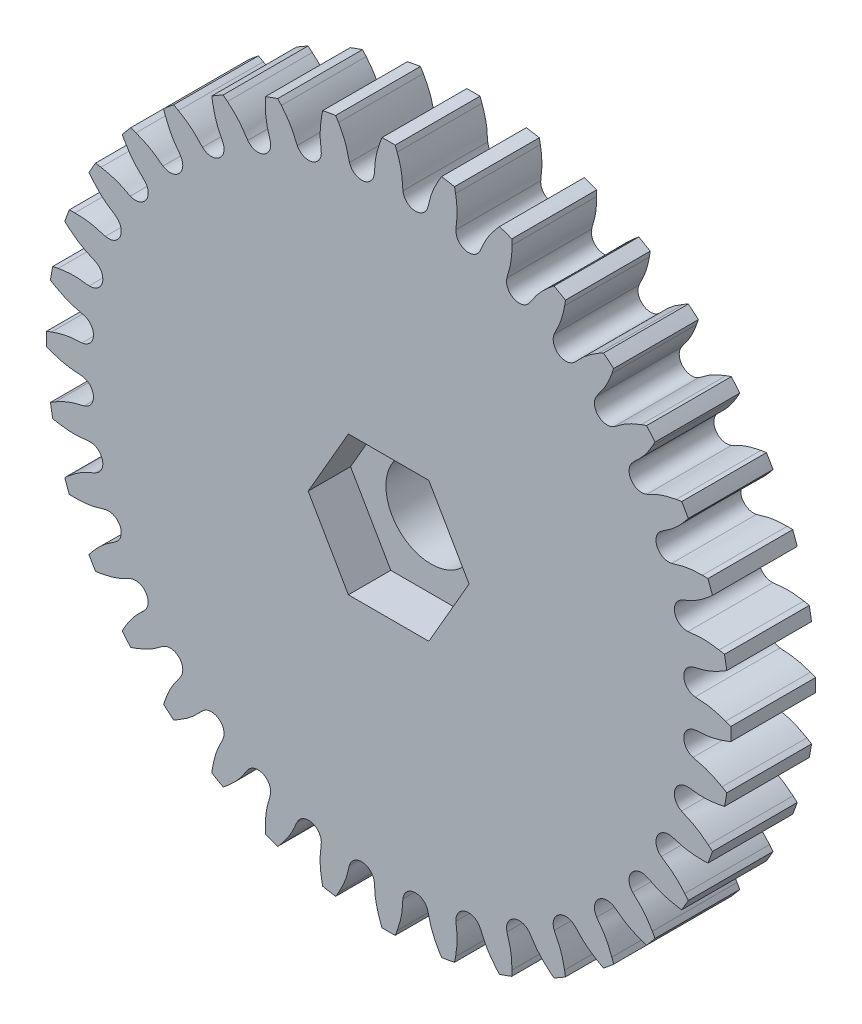
SolidWorks part; units mm, degrees
ref_plane "Front Plane" through (0, 0, 0) normal (0, 0, 1) x (1, 0, 0)
ref_plane "Top Plane" through (0, 0, 0) normal (0, 1, 0) x (1, 0, 0)
ref_plane "Right Plane" through (0, 0, 0) normal (1, 0, 0) x (0, 0, -1)
sketch "Sketch2" plane through (0, 0, 0) normal (0, 0, 1) x (1, 0, 0)
  arc A6 (376.7987, 146.0449) -> (376.5121, 146.0397) centre (376.8028, 137.9746) ccw
  arc A7 (375.8033, 142.7322) -> (375.522, 142.6773) centre (377.2087, 134.7852) ccw
  arc A8 (375.3983, 139.297) -> (375.1308, 139.1941) centre (378.1623, 131.7148) ccw
  arc A9 (375.5959, 135.8437) -> (375.3503, 135.6959) centre (379.6346, 128.8566) ccw
  arc A10 (376.3902, 132.4771) -> (376.174, 132.2889) centre (381.5809, 126.2975) ccw
  arc A11 (377.757, 129.2996) -> (377.5768, 129.0768) centre (383.9419, 124.1153) ccw
  arc A12 (378.0711, 128.2207) -> (378.3542, 128.2653) centre (376.9568, 136.2138) ccw
  arc A13 (379.6549, 126.4078) -> (379.5161, 126.157) centre (386.646, 122.3762) ccw
  arc A14 (380.1515, 125.3998) -> (380.4226, 125.4929) centre (377.6662, 133.0779) ccw
  arc A15 (382.026, 123.8894) -> (381.9329, 123.6183) centre (389.6111, 121.133) ccw
  arc A16 (382.6901, 122.983) -> (382.9409, 123.1217) centre (378.9093, 130.1129) ccw
  arc A17 (384.7985, 121.821) -> (384.7539, 121.5379) centre (392.7469, 120.4237) ccw
  arc A18 (385.6099, 121.0437) -> (385.8328, 121.2239) centre (380.6484, 127.4088) ccw
  arc A19 (388.8221, 119.6409) -> (389.0103, 119.857) centre (382.8307, 125.0477) ccw
  arc A20 (392.229, 118.8172) -> (392.3768, 119.0627) centre (385.3898, 123.1015) ccw
  arc A21 (395.7273, 118.5976) -> (395.8302, 118.8651) centre (388.248, 121.6292) ccw
  arc A22 (399.2105, 118.9888) -> (399.2654, 119.2701) centre (391.3184, 120.6756) ccw
  arc A23 (402.5728, 119.979) -> (402.5781, 120.2655) centre (394.5077, 120.2696) ccw
  arc A24 (394.2909, 120.6779) -> (393.9148, 121.0197) centre (393.8841, 120.6081) ccw
  arc A25 (393.4611, 121.0594) -> (393.0313, 120.7881) centre (393.4199, 120.6488) ccw
  arc A26 (391.1757, 121.1152) -> (390.8647, 121.5173) centre (390.763, 121.1172) ccw
  arc A27 (390.4248, 121.6351) -> (389.9544, 121.4425) centre (390.3129, 121.2378) ccw
  arc A28 (388.1838, 122.0869) -> (387.9473, 122.5368) centre (387.7777, 122.1606) ccw
  arc A29 (387.5346, 122.7293) -> (387.0379, 122.6213) centre (387.3554, 122.3575) ccw
  arc A30 (385.4061, 123.5634) -> (385.2513, 124.0475) centre (385.019, 123.7064) ccw
  arc A31 (384.8783, 124.3088) -> (384.3704, 124.2886) centre (384.6372, 123.9737) ccw
  arc A32 (382.927, 125.4998) -> (382.8586, 126.0034) centre (382.5705, 125.7079) ccw
  arc A33 (382.5366, 126.3255) -> (382.0329, 126.3939) centre (382.241, 126.0374) ccw
  arc A34 (380.8218, 127.8372) -> (380.8419, 128.3451) centre (380.5069, 128.1041) ccw
  arc A35 (380.5807, 128.7182) -> (380.0966, 128.873) centre (380.2396, 128.4858) ccw
  arc A36 (379.1545, 130.5047) -> (379.2625, 131.0014) centre (378.8907, 130.8222) ccw
  arc A37 (379.07, 131.4142) -> (378.6201, 131.6507) centre (378.6937, 131.2446) ccw
  arc A38 (377.9757, 133.4213) -> (378.1683, 133.8916) centre (377.771, 133.7797) ccw
  arc A39 (378.0504, 134.3315) -> (377.6484, 134.6426) centre (377.6504, 134.2298) ccw
  arc A40 (377.3212, 136.4982) -> (377.5926, 136.9279) centre (377.1819, 136.8867) ccw
  arc A41 (377.5529, 137.3816) -> (377.211, 137.7578) centre (377.1413, 137.3509) ccw
  arc A42 (392.3768, 158.337) -> (392.229, 158.5825) centre (385.3898, 154.2983) ccw
  arc A43 (389.0103, 157.5427) -> (388.8221, 157.7588) centre (382.8307, 152.352) ccw
  arc A44 (385.8328, 156.1759) -> (385.6099, 156.356) centre (380.6484, 149.991) ccw
  arc A45 (384.7539, 155.8618) -> (384.7985, 155.5787) centre (392.7469, 156.976) ccw
  arc A46 (382.9409, 154.278) -> (382.6901, 154.4168) centre (378.9093, 147.2869) ccw
  arc A47 (381.9329, 153.7814) -> (382.026, 153.5103) centre (389.6111, 156.2667) ccw
  arc A48 (380.4226, 151.9069) -> (380.1515, 152) centre (377.6662, 144.3218) ccw
  arc A49 (379.5161, 151.2427) -> (379.6549, 150.992) centre (386.646, 155.0236) ccw
  arc A50 (378.3542, 149.1344) -> (378.0711, 149.179) centre (376.9568, 141.186) ccw
  arc A51 (377.5768, 148.323) -> (377.757, 148.1001) centre (383.9419, 153.2845) ccw
  arc A52 (376.174, 145.1108) -> (376.3902, 144.9226) centre (381.5809, 151.1022) ccw
  arc A53 (375.3503, 141.7039) -> (375.5959, 141.556) centre (379.6346, 148.5431) ccw
  arc A54 (375.1308, 138.2056) -> (375.3983, 138.1027) centre (378.1623, 145.6849) ccw
  arc A55 (375.522, 134.7224) -> (375.8033, 134.6675) centre (377.2087, 142.6145) ccw
  arc A56 (376.5121, 131.3601) -> (376.7987, 131.3548) centre (376.8028, 139.4252) ccw
  arc A57 (402.5781, 157.1342) -> (402.5728, 157.4208) centre (394.5077, 157.1301) ccw
  arc A58 (399.2654, 158.1296) -> (399.2105, 158.4109) centre (391.3184, 156.7242) ccw
  arc A59 (395.8302, 158.5346) -> (395.7273, 158.8021) centre (388.248, 155.7705) ccw
  arc A60 (377.211, 139.642) -> (377.5529, 140.0181) centre (377.1413, 140.0488) ccw
  arc A61 (377.5926, 140.4718) -> (377.3212, 140.9016) centre (377.1819, 140.513) ccw
  arc A62 (377.6484, 142.7571) -> (378.0504, 143.0682) centre (377.6504, 143.1699) ccw
  arc A63 (378.1683, 143.5081) -> (377.9757, 143.9785) centre (377.771, 143.62) ccw
  arc A64 (378.6201, 145.749) -> (379.07, 145.9856) centre (378.6937, 146.1552) ccw
  arc A65 (379.2625, 146.3983) -> (379.1545, 146.895) centre (378.8907, 146.5775) ccw
  arc A66 (380.0966, 148.5268) -> (380.5807, 148.6816) centre (380.2396, 148.9139) ccw
  arc A67 (380.8419, 149.0546) -> (380.8218, 149.5625) centre (380.5069, 149.2957) ccw
  arc A68 (382.0329, 151.0059) -> (382.5366, 151.0743) centre (382.241, 151.3623) ccw
  arc A69 (382.8586, 151.3963) -> (382.927, 151.9) centre (382.5705, 151.6919) ccw
  arc A70 (384.3704, 153.1111) -> (384.8783, 153.091) centre (384.6372, 153.426) ccw
  arc A71 (385.2513, 153.3522) -> (385.4061, 153.8363) centre (385.019, 153.6933) ccw
  arc A72 (387.0379, 154.7784) -> (387.5346, 154.6704) centre (387.3554, 155.0422) ccw
  arc A73 (387.9473, 154.8629) -> (388.1838, 155.3128) centre (387.7777, 155.2392) ccw
  arc A74 (389.9544, 155.9572) -> (390.4248, 155.7646) centre (390.3129, 156.1619) ccw
  arc A75 (390.8647, 155.8825) -> (391.1757, 156.2845) centre (390.763, 156.2825) ccw
  arc A76 (393.0313, 156.6117) -> (393.4611, 156.3403) centre (393.4199, 156.751) ccw
  arc A77 (393.9148, 156.38) -> (394.2909, 156.7219) centre (393.8841, 156.7916) ccw
  arc A78 (387.888, 120.2655) -> (387.8932, 119.979) centre (395.9583, 120.2696) ccw
  arc A79 (391.2007, 119.2701) -> (391.2556, 118.9888) centre (399.1477, 120.6756) ccw
  arc A80 (394.6359, 118.8651) -> (394.7388, 118.5976) centre (402.2181, 121.6292) ccw
  arc A81 (398.0892, 119.0627) -> (398.237, 118.8172) centre (405.0763, 123.1015) ccw
  arc A82 (401.4558, 119.857) -> (401.644, 119.6409) centre (407.6354, 125.0477) ccw
  arc A83 (404.6332, 121.2239) -> (404.8561, 121.0437) centre (409.8176, 127.4088) ccw
  arc A84 (405.7122, 121.5379) -> (405.6676, 121.821) centre (397.7191, 120.4237) ccw
  arc A85 (407.5251, 123.1217) -> (407.7759, 122.983) centre (411.5567, 130.1129) ccw
  arc A86 (408.5331, 123.6183) -> (408.44, 123.8894) centre (400.855, 121.133) ccw
  arc A87 (410.0435, 125.4929) -> (410.3146, 125.3998) centre (412.7998, 133.0779) ccw
  arc A88 (410.9499, 126.157) -> (410.8112, 126.4078) centre (403.82, 122.3762) ccw
  arc A89 (412.1119, 128.2653) -> (412.395, 128.2207) centre (413.5092, 136.2138) ccw
  arc A90 (412.8892, 129.0768) -> (412.709, 129.2996) centre (406.5241, 124.1153) ccw
  arc A91 (414.292, 132.2889) -> (414.0758, 132.4771) centre (408.8852, 126.2975) ccw
  arc A92 (415.1157, 135.6959) -> (414.8701, 135.8437) centre (410.8314, 128.8566) ccw
  arc A93 (415.3353, 139.1941) -> (415.0678, 139.297) centre (412.3037, 131.7148) ccw
  arc A94 (414.9441, 142.6773) -> (414.6628, 142.7322) centre (413.2573, 134.7852) ccw
  arc A95 (413.9539, 146.0397) -> (413.6674, 146.0449) centre (413.6633, 137.9746) ccw
  arc A96 (413.255, 137.7578) -> (412.9131, 137.3816) centre (413.3248, 137.3509) ccw
  arc A97 (412.8735, 136.9279) -> (413.1448, 136.4982) centre (413.2841, 136.8867) ccw
  arc A98 (412.8176, 134.6426) -> (412.4156, 134.3315) centre (412.8157, 134.2298) ccw
  arc A99 (412.2978, 133.8916) -> (412.4904, 133.4213) centre (412.695, 133.7797) ccw
  arc A100 (411.846, 131.6507) -> (411.396, 131.4142) centre (411.7723, 131.2446) ccw
  arc A101 (411.2036, 131.0014) -> (411.3116, 130.5047) centre (411.5754, 130.8222) ccw
  arc A102 (410.3695, 128.873) -> (409.8853, 128.7182) centre (410.2265, 128.4858) ccw
  arc A103 (409.6241, 128.3451) -> (409.6443, 127.8372) centre (409.9592, 128.1041) ccw
  arc A104 (408.4331, 126.3939) -> (407.9294, 126.3255) centre (408.225, 126.0374) ccw
  arc A105 (407.6074, 126.0034) -> (407.539, 125.4998) centre (407.8955, 125.7079) ccw
  arc A106 (406.0957, 124.2886) -> (405.5878, 124.3088) centre (405.8288, 123.9737) ccw
  arc A107 (405.2147, 124.0475) -> (405.0599, 123.5634) centre (405.4471, 123.7064) ccw
  arc A108 (403.4281, 122.6213) -> (402.9315, 122.7293) centre (403.1107, 122.3575) ccw
  arc A109 (402.5187, 122.5368) -> (402.2822, 122.0869) centre (402.6883, 122.1606) ccw
  arc A110 (400.5116, 121.4425) -> (400.0413, 121.6351) centre (400.1532, 121.2378) ccw
  arc A111 (399.6013, 121.5173) -> (399.2903, 121.1152) centre (399.703, 121.1172) ccw
  arc A112 (397.4347, 120.7881) -> (397.0049, 121.0594) centre (397.0462, 120.6488) ccw
  arc A113 (396.5513, 121.0197) -> (396.1751, 120.6779) centre (396.5819, 120.6081) ccw
  arc A114 (398.237, 118.8172) -> (399.2105, 118.9888) centre (395.233, 138.6999) ccw
  arc A115 (401.644, 119.6409) -> (402.5728, 119.979) centre (395.233, 138.6999) ccw
  arc A116 (404.8561, 121.0437) -> (405.7122, 121.5379) centre (395.233, 138.6999) ccw
  arc A117 (410.3146, 125.3998) -> (410.9499, 126.157) centre (395.233, 138.6999) ccw
  arc A118 (412.395, 128.2207) -> (412.8892, 129.0768) centre (395.233, 138.6999) ccw
  arc A119 (414.9441, 134.7224) -> (415.1157, 135.6959) centre (395.233, 138.6999) ccw
  arc A120 (415.1157, 141.7039) -> (414.9441, 142.6773) centre (395.233, 138.6999) ccw
  arc A121 (412.8892, 148.323) -> (412.395, 149.179) centre (395.233, 138.6999) ccw
  arc A122 (410.9499, 151.2427) -> (410.3146, 152) centre (395.233, 138.6999) ccw
  arc A123 (408.5331, 153.7814) -> (407.7759, 154.4168) centre (395.233, 138.6999) ccw
  arc A124 (402.5728, 157.4208) -> (401.644, 157.7588) centre (395.233, 138.6999) ccw
  arc A125 (391.2556, 118.9888) -> (392.229, 118.8172) centre (395.233, 138.6999) ccw
  arc A126 (387.8932, 119.979) -> (388.8221, 119.6409) centre (395.233, 138.6999) ccw
  arc A127 (379.5161, 126.157) -> (380.1515, 125.3998) centre (395.233, 138.6999) ccw
  arc A128 (377.5768, 129.0768) -> (378.0711, 128.2207) centre (395.233, 138.6999) ccw
  arc A129 (375.522, 142.6773) -> (375.3503, 141.7039) centre (395.233, 138.6999) ccw
  arc A130 (385.6099, 156.356) -> (384.7539, 155.8618) centre (395.233, 138.6999) ccw
  arc A131 (392.229, 158.5825) -> (391.2556, 158.4109) centre (395.233, 138.6999) ccw
  arc A132 (394.7388, 118.5976) -> (395.7273, 118.5976) centre (395.233, 138.6999) ccw
  arc A133 (407.7759, 122.983) -> (408.5331, 123.6183) centre (395.233, 138.6999) ccw
  arc A134 (413.9539, 131.3601) -> (414.292, 132.2889) centre (395.233, 138.6999) ccw
  arc A135 (415.3353, 138.2056) -> (415.3353, 139.1941) centre (395.233, 138.6999) ccw
  arc A136 (414.292, 145.1108) -> (413.9539, 146.0397) centre (395.233, 138.6999) ccw
  arc A137 (405.7122, 155.8618) -> (404.8561, 156.356) centre (395.233, 138.6999) ccw
  arc A138 (399.2105, 158.4109) -> (398.237, 158.5825) centre (395.233, 138.6999) ccw
  arc A139 (395.7273, 158.8021) -> (394.7388, 158.8021) centre (395.233, 138.6999) ccw
  arc A140 (384.7539, 121.5379) -> (385.6099, 121.0437) centre (395.233, 138.6999) ccw
  arc A141 (381.9329, 123.6183) -> (382.6901, 122.983) centre (395.233, 138.6999) ccw
  arc A142 (376.174, 132.2889) -> (376.5121, 131.3601) centre (395.233, 138.6999) ccw
  arc A143 (375.3503, 135.6959) -> (375.522, 134.7224) centre (395.233, 138.6999) ccw
  arc A144 (375.1308, 139.1941) -> (375.1308, 138.2056) centre (395.233, 138.6999) ccw
  arc A145 (376.5121, 146.0397) -> (376.174, 145.1108) centre (395.233, 138.6999) ccw
  arc A146 (378.0711, 149.179) -> (377.5768, 148.323) centre (395.233, 138.6999) ccw
  arc A147 (380.1515, 152) -> (379.5161, 151.2427) centre (395.233, 138.6999) ccw
  arc A148 (382.6901, 154.4168) -> (381.9329, 153.7814) centre (395.233, 138.6999) ccw
  arc A149 (388.8221, 157.7588) -> (387.8932, 157.4208) centre (395.233, 138.6999) ccw
  arc A150 (375.1247, 138.6999) -> (376.174, 132.2889) centre (395.233, 138.6999) ccw
  arc A151 (376.2323, 132.1183) -> (376.2519, 132.062) centre (395.233, 138.6999) ccw
  arc A152 (376.5121, 131.3601) -> (377.612, 129.0126) centre (395.233, 138.6999) ccw
  arc A153 (377.6257, 128.9877) -> (378.0184, 128.3076) centre (395.233, 138.6999) ccw
  arc A154 (378.0331, 128.2832) -> (382.4053, 123.2146) centre (395.233, 138.6999) ccw
  arc A155 (382.4053, 123.2146) -> (385.2068, 121.2694) centre (395.233, 138.6999) ccw
  arc A156 (385.6099, 121.0437) -> (387.8932, 119.979) centre (395.233, 138.6999) ccw
  arc A157 (388.2176, 119.855) -> (388.2362, 119.8481) centre (395.233, 138.6999) ccw
  arc A158 (388.8221, 119.6409) -> (391.2556, 118.9888) centre (395.233, 138.6999) ccw
  arc A159 (391.4324, 118.954) -> (394.7388, 118.5976) centre (395.233, 138.6999) ccw
  arc A160 (394.8404, 118.5954) -> (395.6541, 118.5959) centre (395.233, 138.6999) ccw
  arc A161 (395.7273, 118.5976) -> (398.237, 118.8172) centre (395.233, 138.6999) ccw
  arc A162 (399.2105, 118.9888) -> (401.644, 119.6409) centre (395.233, 138.6999) ccw
  arc A163 (402.5728, 119.979) -> (405.2593, 121.2694) centre (395.233, 138.6999) ccw
  arc A164 (405.7122, 121.5379) -> (408.0455, 123.2019) centre (395.233, 138.6999) ccw
  arc A165 (408.5331, 123.6183) -> (410.3146, 125.3998) centre (395.233, 138.6999) ccw
  arc A166 (410.9499, 126.157) -> (412.4235, 128.2676) centre (395.233, 138.6999) ccw
  arc A167 (412.8541, 129.0126) -> (412.8629, 129.0286) centre (395.233, 138.6999) ccw
  arc A168 (412.8892, 129.0768) -> (413.9539, 131.3601) centre (395.233, 138.6999) ccw
  arc A169 (414.292, 132.2889) -> (414.9441, 134.7224) centre (395.233, 138.6999) ccw
  arc A170 (415.1157, 135.6959) -> (415.3353, 138.2056) centre (395.233, 138.6999) ccw
  arc A171 (415.3353, 139.1941) -> (415.0575, 142.0664) centre (395.233, 138.6999) ccw
  arc A172 (414.9441, 142.6773) -> (414.292, 145.1108) centre (395.233, 138.6999) ccw
  arc A173 (414.2338, 145.2814) -> (414.2142, 145.3377) centre (395.233, 138.6999) ccw
  arc A174 (413.9539, 146.0397) -> (412.8541, 148.3871) centre (395.233, 138.6999) ccw
  arc A175 (412.8404, 148.4121) -> (412.4477, 149.0922) centre (395.233, 138.6999) ccw
  arc A176 (412.433, 149.1165) -> (412.4235, 149.1322) centre (395.233, 138.6999) ccw
  arc A177 (412.395, 149.179) -> (410.9499, 151.2427) centre (395.233, 138.6999) ccw
  arc A178 (410.4332, 151.8642) -> (408.5331, 153.7814) centre (395.233, 138.6999) ccw
  arc A179 (408.0608, 154.1852) -> (405.7122, 155.8618) centre (395.233, 138.6999) ccw
  arc A180 (404.8561, 156.356) -> (402.5728, 157.4208) centre (395.233, 138.6999) ccw
  arc A181 (401.644, 157.7588) -> (399.2105, 158.4109) centre (395.233, 138.6999) ccw
  arc A182 (399.0336, 158.4458) -> (395.6541, 158.8038) centre (395.233, 138.6999) ccw
  arc A183 (395.6257, 158.8044) -> (394.8119, 158.8038) centre (395.233, 138.6999) ccw
  arc A184 (394.8119, 158.8038) -> (391.491, 158.4569) centre (395.233, 138.6999) ccw
  arc A185 (391.2556, 158.4109) -> (388.8221, 157.7589) centre (395.233, 138.6999) ccw
  arc A186 (388.2362, 157.5517) -> (380.0329, 151.8642) centre (395.233, 138.6999) ccw
  arc A187 (379.9939, 151.8191) -> (376.2519, 145.3377) centre (395.233, 138.6999) ccw
  arc A188 (376.174, 145.1108) -> (375.522, 142.6773) centre (395.233, 138.6999) ccw
  arc A189 (375.4085, 142.0664) -> (375.1308, 139.1941) centre (395.233, 138.6999) ccw
  arc A190 (376.2011, 137.8703) -> (376.3461, 136.2124) centre (395.233, 138.6999) ccw
  arc A191 (376.6344, 134.5774) -> (377.0649, 132.9709) centre (395.233, 138.6999) ccw
  arc A192 (377.6329, 131.4102) -> (378.3356, 129.9033) centre (395.233, 138.6999) ccw
  arc A193 (379.1662, 128.4647) -> (380.1199, 127.1027) centre (395.233, 138.6999) ccw
  arc A194 (381.1875, 125.8303) -> (382.3635, 124.6543) centre (395.233, 138.6999) ccw
  arc A195 (383.6353, 123.5871) -> (384.9985, 122.6326) centre (395.233, 138.6999) ccw
  arc A196 (386.4355, 121.8029) -> (387.9438, 121.0996) centre (395.233, 138.6999) ccw
  arc A197 (389.5038, 120.5318) -> (391.1104, 120.1013) centre (395.233, 138.6999) ccw
  arc A198 (392.746, 119.8129) -> (394.4024, 119.668) centre (395.233, 138.6999) ccw
  arc A199 (396.0636, 119.668) -> (397.7199, 119.8129) centre (395.233, 138.6999) ccw
  arc A200 (399.3556, 120.1013) -> (400.9621, 120.5318) centre (395.233, 138.6999) ccw
  arc A201 (402.5222, 121.0996) -> (404.0305, 121.8029) centre (395.233, 138.6999) ccw
  arc A202 (405.4675, 122.6325) -> (406.8307, 123.5871) centre (395.233, 138.6999) ccw
  arc A203 (408.1025, 124.6542) -> (409.2785, 125.8303) centre (395.233, 138.6999) ccw
  arc A204 (410.3461, 127.1026) -> (411.2998, 128.4646) centre (395.233, 138.6999) ccw
  arc A205 (412.1304, 129.9032) -> (412.8331, 131.4101) centre (395.233, 138.6999) ccw
  arc A206 (413.4011, 132.9708) -> (413.8316, 134.5774) centre (395.233, 138.6999) ccw
  arc A207 (414.1199, 136.2123) -> (414.2649, 137.8702) centre (395.233, 138.6999) ccw
  arc A208 (414.265, 139.5295) -> (414.1199, 141.1874) centre (395.233, 138.6999) ccw
  arc A209 (413.8316, 142.8223) -> (413.4012, 144.4288) centre (395.233, 138.6999) ccw
  arc A210 (412.8331, 145.9896) -> (412.1304, 147.4965) centre (395.233, 138.6999) ccw
  arc A211 (411.2999, 148.9351) -> (410.3462, 150.2971) centre (395.233, 138.6999) ccw
  arc A212 (409.2786, 151.5694) -> (408.1025, 152.7455) centre (395.233, 138.6999) ccw
  arc A213 (406.8308, 153.8126) -> (405.4675, 154.7672) centre (395.233, 138.6999) ccw
  arc A214 (404.0305, 155.5968) -> (402.5222, 156.3001) centre (395.233, 138.6999) ccw
  arc A215 (400.9622, 156.8679) -> (399.3557, 157.2984) centre (395.233, 138.6999) ccw
  arc A216 (397.72, 157.5868) -> (396.0636, 157.7318) centre (395.233, 138.6999) ccw
  arc A217 (394.4025, 157.7318) -> (392.7461, 157.5868) centre (395.233, 138.6999) ccw
  arc A218 (391.1105, 157.2984) -> (389.5039, 156.868) centre (395.233, 138.6999) ccw
  arc A219 (387.9439, 156.3002) -> (386.4356, 155.5968) centre (395.233, 138.6999) ccw
  arc A220 (384.9986, 154.7672) -> (383.6353, 153.8127) centre (395.233, 138.6999) ccw
  arc A221 (382.3636, 152.7455) -> (381.1875, 151.5695) centre (395.233, 138.6999) ccw
  arc A222 (380.1199, 150.2971) -> (379.1662, 148.9351) centre (395.233, 138.6999) ccw
  arc A223 (378.3357, 147.4966) -> (377.633, 145.9896) centre (395.233, 138.6999) ccw
  arc A224 (377.0649, 144.4289) -> (376.6344, 142.8224) centre (395.233, 138.6999) ccw
  arc A225 (376.3461, 141.1874) -> (376.2011, 139.5296) centre (395.233, 138.6999) ccw
  arc A226 (376.8121, 137.793) -> (376.9345, 136.3939) centre (395.233, 138.6999) ccw
  arc A227 (377.2495, 134.6079) -> (377.6129, 133.2516) centre (395.233, 138.6999) ccw
  arc A228 (378.2332, 131.5473) -> (378.8266, 130.2748) centre (395.233, 138.6999) ccw
  arc A229 (379.7335, 128.704) -> (380.5389, 127.5539) centre (395.233, 138.6999) ccw
  arc A230 (381.7047, 126.1645) -> (382.6976, 125.1716) centre (395.233, 138.6999) ccw
  arc A231 (384.0868, 124.0058) -> (385.2373, 123.2003) centre (395.233, 138.6999) ccw
  arc A232 (386.8079, 122.2935) -> (388.0808, 121.6999) centre (395.233, 138.6999) ccw
  arc A233 (389.785, 121.0797) -> (391.1413, 120.7163) centre (395.233, 138.6999) ccw
  arc A234 (392.9274, 120.4013) -> (394.3262, 120.279) centre (395.233, 138.6999) ccw
  arc A235 (396.1399, 120.279) -> (397.5387, 120.4013) centre (395.233, 138.6999) ccw
  arc A236 (399.3248, 120.7163) -> (400.6812, 121.0797) centre (395.233, 138.6999) ccw
  arc A237 (402.3853, 121.7) -> (403.6582, 122.2935) centre (395.233, 138.6999) ccw
  arc A238 (405.2288, 123.2003) -> (406.3793, 124.0059) centre (395.233, 138.6999) ccw
  arc A239 (407.7685, 125.1716) -> (408.7614, 126.1645) centre (395.233, 138.6999) ccw
  arc A240 (409.9272, 127.5539) -> (410.7326, 128.7041) centre (395.233, 138.6999) ccw
  arc A241 (411.6394, 130.2748) -> (412.2328, 131.5474) centre (395.233, 138.6999) ccw
  arc A242 (412.8532, 133.2517) -> (413.2166, 134.608) centre (395.233, 138.6999) ccw
  arc A243 (413.5315, 136.394) -> (413.6539, 137.7931) centre (395.233, 138.6999) ccw
  arc A244 (413.6539, 139.6067) -> (413.5315, 141.0058) centre (395.233, 138.6999) ccw
  arc A245 (413.2166, 142.7918) -> (412.8531, 144.1481) centre (395.233, 138.6999) ccw
  arc A246 (412.2328, 145.8524) -> (411.6394, 147.125) centre (395.233, 138.6999) ccw
  arc A247 (410.7325, 148.6957) -> (409.9272, 149.8459) centre (395.233, 138.6999) ccw
  arc A248 (408.7614, 151.2352) -> (407.7685, 152.2282) centre (395.233, 138.6999) ccw
  arc A249 (406.3792, 153.3939) -> (405.2288, 154.1994) centre (395.233, 138.6999) ccw
  arc A250 (403.6581, 155.1063) -> (402.3853, 155.6998) centre (395.233, 138.6999) ccw
  arc A251 (400.6811, 156.32) -> (399.3247, 156.6835) centre (395.233, 138.6999) ccw
  arc A252 (397.5386, 156.9984) -> (396.1399, 157.1208) centre (395.233, 138.6999) ccw
  arc A253 (394.3261, 157.1208) -> (392.9274, 156.9984) centre (395.233, 138.6999) ccw
  arc A254 (391.1412, 156.6835) -> (389.7849, 156.32) centre (395.233, 138.6999) ccw
  arc A255 (388.0807, 155.6998) -> (386.8079, 155.1062) centre (395.233, 138.6999) ccw
  arc A256 (385.2372, 154.1994) -> (384.0868, 153.3939) centre (395.233, 138.6999) ccw
  arc A257 (382.6975, 152.2281) -> (381.7046, 151.2352) centre (395.233, 138.6999) ccw
  arc A258 (380.5388, 149.8458) -> (379.7335, 148.6957) centre (395.233, 138.6999) ccw
  arc A259 (378.8266, 147.1249) -> (378.2332, 145.8524) centre (395.233, 138.6999) ccw
  arc A260 (377.6129, 144.1481) -> (377.2495, 142.7917) centre (395.233, 138.6999) ccw
  arc A261 (376.9345, 141.0057) -> (376.8121, 139.6067) centre (395.233, 138.6999) ccw
  arc A262 (377.2669, 137.7424) -> (377.3736, 136.5225) centre (395.233, 138.6999) ccw
  arc A263 (377.7061, 134.6369) -> (378.0231, 133.4541) centre (395.233, 138.6999) ccw
  arc A264 (378.6779, 131.6552) -> (379.1952, 130.5459) centre (395.233, 138.6999) ccw
  arc A265 (380.1525, 128.8877) -> (380.8546, 127.8851) centre (395.233, 138.6999) ccw
  arc A266 (382.0851, 126.4185) -> (382.9509, 125.5526) centre (395.233, 138.6999) ccw
  arc A267 (384.4177, 124.3218) -> (385.4207, 123.6195) centre (395.233, 138.6999) ccw
  arc A268 (387.0792, 122.662) -> (388.189, 122.1445) centre (395.233, 138.6999) ccw
  arc A269 (389.9882, 121.4896) -> (391.171, 121.1728) centre (395.233, 138.6999) ccw
  arc A270 (393.0564, 120.8404) -> (394.2757, 120.7337) centre (395.233, 138.6999) ccw
  arc A271 (396.1904, 120.7337) -> (397.4097, 120.8404) centre (395.233, 138.6999) ccw
  arc A272 (399.2951, 121.1728) -> (400.4778, 121.4896) centre (395.233, 138.6999) ccw
  arc A273 (402.2771, 122.1445) -> (403.3869, 122.662) centre (395.233, 138.6999) ccw
  arc A274 (405.0453, 123.6195) -> (406.0484, 124.3218) centre (395.233, 138.6999) ccw
  arc A275 (407.5151, 125.5526) -> (408.3809, 126.4185) centre (395.233, 138.6999) ccw
  arc A276 (409.6115, 127.8851) -> (410.3135, 128.8877) centre (395.233, 138.6999) ccw
  arc A277 (411.2709, 130.5459) -> (411.7881, 131.6552) centre (395.233, 138.6999) ccw
  arc A278 (412.443, 133.4541) -> (412.7599, 134.6369) centre (395.233, 138.6999) ccw
  arc A279 (413.0925, 136.5225) -> (413.1992, 137.7424) centre (395.233, 138.6999) ccw
  arc A280 (413.1992, 139.6574) -> (413.0925, 140.8772) centre (395.233, 138.6999) ccw
  arc A281 (412.7599, 142.7628) -> (412.443, 143.9456) centre (395.233, 138.6999) ccw
  arc A282 (411.7881, 145.7446) -> (411.2709, 146.8539) centre (395.233, 138.6999) ccw
  arc A283 (410.3135, 148.5121) -> (409.6115, 149.5147) centre (395.233, 138.6999) ccw
  arc A284 (408.3809, 150.9813) -> (407.5151, 151.8471) centre (395.233, 138.6999) ccw
  arc A285 (406.0484, 153.0779) -> (405.0453, 153.7803) centre (395.233, 138.6999) ccw
  arc A286 (403.3869, 154.7378) -> (402.2771, 155.2553) centre (395.233, 138.6999) ccw
  arc A287 (400.4778, 155.9101) -> (399.2951, 156.227) centre (395.233, 138.6999) ccw
  arc A288 (397.4097, 156.5594) -> (396.1904, 156.666) centre (395.233, 138.6999) ccw
  arc A289 (394.2757, 156.666) -> (393.0564, 156.5594) centre (395.233, 138.6999) ccw
  arc A290 (391.171, 156.227) -> (389.9882, 155.9101) centre (395.233, 138.6999) ccw
  arc A291 (388.189, 155.2553) -> (387.0792, 154.7378) centre (395.233, 138.6999) ccw
  arc A292 (385.4207, 153.7803) -> (384.4177, 153.0779) centre (395.233, 138.6999) ccw
  arc A293 (382.9509, 151.8471) -> (382.0851, 150.9813) centre (395.233, 138.6999) ccw
  arc A294 (380.8546, 149.5147) -> (380.1525, 148.5121) centre (395.233, 138.6999) ccw
  arc A295 (379.1952, 146.8539) -> (378.6779, 145.7446) centre (395.233, 138.6999) ccw
  arc A296 (378.0231, 143.9456) -> (377.7061, 142.7628) centre (395.233, 138.6999) ccw
  arc A297 (377.3736, 140.8772) -> (377.2669, 139.6574) centre (395.233, 138.6999) ccw
  arc A298 (397.0049, 156.3403) -> (396.5513, 156.38) centre (395.233, 138.6999) ccw
  arc A299 (400.0413, 155.7646) -> (399.6013, 155.8825) centre (395.233, 138.6999) ccw
  arc A300 (393.9148, 156.38) -> (393.4611, 156.3403) centre (395.233, 138.6999) ccw
  arc A301 (390.8647, 155.8825) -> (390.4248, 155.7646) centre (395.233, 138.6999) ccw
  arc A302 (387.9473, 154.8629) -> (387.5346, 154.6704) centre (395.233, 138.6999) ccw
  arc A303 (402.9315, 154.6704) -> (402.5187, 154.8629) centre (395.233, 138.6999) ccw
  arc A304 (385.2513, 153.3522) -> (384.8783, 153.091) centre (395.233, 138.6999) ccw
  arc A305 (382.8586, 151.3963) -> (382.5366, 151.0743) centre (395.233, 138.6999) ccw
  arc A306 (380.8419, 149.0546) -> (380.5807, 148.6816) centre (395.233, 138.6999) ccw
  arc A307 (405.5878, 153.091) -> (405.2147, 153.3522) centre (395.233, 138.6999) ccw
  arc A308 (379.2625, 146.3983) -> (379.07, 145.9856) centre (395.233, 138.6999) ccw
  arc A309 (378.1683, 143.5081) -> (378.0504, 143.0682) centre (395.233, 138.6999) ccw
  arc A310 (377.5926, 140.4718) -> (377.5529, 140.0181) centre (395.233, 138.6999) ccw
  arc A311 (407.9294, 151.0743) -> (407.6074, 151.3963) centre (395.233, 138.6999) ccw
  arc A312 (377.5529, 137.3816) -> (377.5926, 136.9279) centre (395.233, 138.6999) ccw
  arc A313 (378.0504, 134.3315) -> (378.1683, 133.8916) centre (395.233, 138.6999) ccw
  arc A314 (379.07, 131.4142) -> (379.2625, 131.0014) centre (395.233, 138.6999) ccw
  arc A315 (409.8853, 148.6816) -> (409.6241, 149.0546) centre (395.233, 138.6999) ccw
  arc A316 (380.5807, 128.7182) -> (380.8419, 128.3451) centre (395.233, 138.6999) ccw
  arc A317 (382.5366, 126.3255) -> (382.8586, 126.0034) centre (395.233, 138.6999) ccw
  arc A318 (384.8783, 124.3088) -> (385.2513, 124.0475) centre (395.233, 138.6999) ccw
  arc A319 (411.396, 145.9856) -> (411.2036, 146.3983) centre (395.233, 138.6999) ccw
  arc A320 (387.5346, 122.7293) -> (387.9473, 122.5368) centre (395.233, 138.6999) ccw
  arc A321 (390.4248, 121.6351) -> (390.8647, 121.5173) centre (395.233, 138.6999) ccw
  arc A322 (393.4611, 121.0594) -> (393.9148, 121.0197) centre (395.233, 138.6999) ccw
  arc A323 (412.4156, 143.0682) -> (412.2978, 143.5081) centre (395.233, 138.6999) ccw
  arc A324 (396.5513, 121.0197) -> (397.0049, 121.0594) centre (395.233, 138.6999) ccw
  arc A325 (399.6013, 121.5173) -> (400.0413, 121.6351) centre (395.233, 138.6999) ccw
  arc A326 (402.5187, 122.5368) -> (402.9315, 122.7293) centre (395.233, 138.6999) ccw
  arc A327 (412.9131, 140.0181) -> (412.8735, 140.4718) centre (395.233, 138.6999) ccw
  arc A328 (405.2147, 124.0475) -> (405.5878, 124.3088) centre (395.233, 138.6999) ccw
  arc A329 (407.6074, 126.0034) -> (407.9294, 126.3255) centre (395.233, 138.6999) ccw
  arc A330 (409.6241, 128.3451) -> (409.8853, 128.7182) centre (395.233, 138.6999) ccw
  arc A331 (412.8735, 136.9279) -> (412.9131, 137.3816) centre (395.233, 138.6999) ccw
  arc A332 (411.2036, 131.0014) -> (411.396, 131.4142) centre (395.233, 138.6999) ccw
  arc A333 (412.2978, 133.8916) -> (412.4156, 134.3315) centre (395.233, 138.6999) ccw
  circle A334 centre (395.233, 138.6999) radius 7.9375
  circle A335 centre (395.233, 138.6999) radius 7.6994
  circle A336 centre (395.233, 138.6999) radius 3.4131
  circle A337 centre (395.233, 138.6999) radius 3.175
  arc A338 (391.2556, 158.4109) -> (391.2007, 158.1296) centre (399.1477, 156.7242) ccw
  arc A339 (387.8932, 157.4208) -> (387.888, 157.1342) centre (395.9583, 157.1301) ccw
  arc A340 (410.8112, 150.992) -> (410.9499, 151.2427) centre (403.82, 155.0236) ccw
  arc A341 (408.44, 153.5103) -> (408.5331, 153.7814) centre (400.855, 156.2667) ccw
  arc A342 (405.6676, 155.5787) -> (405.7122, 155.8618) centre (397.7191, 156.976) ccw
  arc A343 (394.7388, 158.8021) -> (394.6359, 158.5346) centre (402.2181, 155.7705) ccw
  arc A344 (396.1751, 156.7219) -> (396.5513, 156.38) centre (396.5819, 156.7916) ccw
  arc A345 (397.0049, 156.3403) -> (397.4347, 156.6117) centre (397.0462, 156.751) ccw
  arc A346 (399.2903, 156.2845) -> (399.6013, 155.8825) centre (399.703, 156.2825) ccw
  arc A347 (400.0413, 155.7646) -> (400.5116, 155.9572) centre (400.1532, 156.1619) ccw
  arc A348 (402.2822, 155.3128) -> (402.5187, 154.8629) centre (402.6883, 155.2392) ccw
  arc A349 (402.9315, 154.6704) -> (403.4281, 154.7784) centre (403.1107, 155.0422) ccw
  arc A350 (413.6674, 131.3548) -> (413.9539, 131.3601) centre (413.6633, 139.4252) ccw
  arc A351 (414.6628, 134.6675) -> (414.9441, 134.7224) centre (413.2573, 142.6145) ccw
  arc A352 (415.0678, 138.1027) -> (415.3353, 138.2056) centre (412.3037, 145.6849) ccw
  arc A353 (412.395, 149.179) -> (412.1119, 149.1344) centre (413.5092, 141.186) ccw
  arc A354 (410.3146, 152) -> (410.0435, 151.9069) centre (412.7998, 144.3218) ccw
  arc A355 (407.7759, 154.4168) -> (407.5251, 154.278) centre (411.5567, 147.2869) ccw
  arc A356 (411.3116, 146.895) -> (411.2036, 146.3983) centre (411.5754, 146.5775) ccw
  arc A357 (411.396, 145.9856) -> (411.846, 145.749) centre (411.7723, 146.1552) ccw
  arc A358 (412.4904, 143.9785) -> (412.2978, 143.5081) centre (412.695, 143.62) ccw
  arc A359 (412.4156, 143.0682) -> (412.8176, 142.7571) centre (412.8157, 143.1699) ccw
  arc A360 (413.1448, 140.9016) -> (412.8735, 140.4718) centre (413.2841, 140.513) ccw
  arc A361 (412.9131, 140.0181) -> (413.255, 139.642) centre (413.3248, 140.0488) ccw
  arc A362 (414.8701, 141.556) -> (415.1157, 141.7039) centre (410.8314, 148.5431) ccw
  arc A363 (414.0758, 144.9226) -> (414.292, 145.1108) centre (408.8852, 151.1022) ccw
  arc A364 (412.709, 148.1001) -> (412.8892, 148.323) centre (406.5241, 153.2845) ccw
  arc A365 (404.8561, 156.356) -> (404.6332, 156.1759) centre (409.8176, 149.991) ccw
  arc A366 (401.644, 157.7588) -> (401.4558, 157.5427) centre (407.6354, 152.352) ccw
  arc A367 (398.237, 158.5825) -> (398.0892, 158.337) centre (405.0763, 154.2983) ccw
  arc A368 (405.0599, 153.8363) -> (405.2147, 153.3522) centre (405.4471, 153.6933) ccw
  arc A369 (405.5878, 153.091) -> (406.0957, 153.1111) centre (405.8288, 153.426) ccw
  arc A370 (407.539, 151.9) -> (407.6074, 151.3963) centre (407.8955, 151.6919) ccw
  arc A371 (407.9294, 151.0743) -> (408.4331, 151.0059) centre (408.225, 151.3623) ccw
  arc A372 (409.6443, 149.5625) -> (409.6241, 149.0546) centre (409.9592, 149.2957) ccw
  arc A373 (409.8853, 148.6816) -> (410.3695, 148.5268) centre (410.2265, 148.9139) ccw
  spline S136 degree 3 poles (396.1751, 156.7219) (396.1721, 156.7393) (396.1599, 156.8139) (396.1432, 156.9467) (396.1397, 157.1208) (396.1362, 157.2949) (396.1144, 157.4678) (396.0828, 157.6389) (396.0469, 157.8092) (396.0056, 157.9783) (395.9592, 158.146) (395.9078, 158.3123) (395.8637, 158.4415) (395.8372, 158.5154) (395.8302, 158.5346) knots 0 0 0 0 0.028535 0.122358 0.216184 0.31001 0.403834 0.497672 0.591513 0.685353 0.779194 0.873034 0.966875 1 1 1 1
  spline S137 degree 3 poles (398.0892, 158.337) (398.079, 158.3193) (398.04, 158.2511) (397.9741, 158.1316) (397.8946, 157.9767) (397.8198, 157.8196) (397.7498, 157.6602) (397.6849, 157.4987) (397.6241, 157.3357) (397.5726, 157.1692) (397.5389, 156.9984) (397.5052, 156.8275) (397.4657, 156.6997) (397.4407, 156.6283) (397.4347, 156.6117) knots 0 0 0 0 0.033125 0.126966 0.220806 0.314647 0.408487 0.502328 0.596166 0.68999 0.783816 0.877642 0.971465 1 1 1 1
  spline S138 degree 3 poles (399.2903, 156.2845) (399.2904, 156.3021) (399.2913, 156.3778) (399.2979, 156.5115) (399.3246, 156.6835) (399.3514, 156.8555) (399.36, 157.0296) (399.3586, 157.2036) (399.3529, 157.3776) (399.3415, 157.5512) (399.325, 157.7245) (399.3033, 157.8972) (399.2823, 158.0321) (399.2689, 158.1094) (399.2654, 158.1296) knots 0 0 0 0 0.028535 0.122358 0.216184 0.31001 0.403834 0.497672 0.591513 0.685353 0.779194 0.873034 0.966875 1 1 1 1
  spline S139 degree 3 poles (401.4558, 157.5427) (401.4426, 157.527) (401.3924, 157.4667) (401.3068, 157.3604) (401.2016, 157.2217) (401.1006, 157.0799) (401.004, 156.9351) (400.912, 156.7874) (400.8238, 156.6374) (400.7442, 156.4823) (400.6814, 156.32) (400.6186, 156.1576) (400.5574, 156.0385) (400.5204, 155.9726) (400.5116, 155.9572) knots 0 0 0 0 0.033125 0.126966 0.220806 0.314647 0.408487 0.502328 0.596166 0.68999 0.783816 0.877642 0.971465 1 1 1 1
  spline S140 degree 3 poles (402.2822, 155.3128) (402.2853, 155.3302) (402.2994, 155.4045) (402.3291, 155.535) (402.3853, 155.6998) (402.4416, 155.8645) (402.4802, 156.0345) (402.5091, 156.2061) (402.5336, 156.3784) (402.5526, 156.5514) (402.5664, 156.7249) (402.575, 156.8988) (402.5778, 157.0352) (402.5781, 157.1137) (402.5781, 157.1342) knots 0 0 0 0 0.028535 0.122358 0.216184 0.31001 0.403834 0.497672 0.591513 0.685353 0.779194 0.873034 0.966875 1 1 1 1
  spline S141 degree 3 poles (404.6332, 156.1759) (404.6176, 156.1627) (404.5576, 156.112) (404.4549, 156.0222) (404.3272, 155.9039) (404.2032, 155.7818) (404.0828, 155.656) (403.9666, 155.5264) (403.8537, 155.394) (403.7484, 155.2552) (403.6583, 155.1062) (403.5682, 154.9572) (403.4873, 154.8505) (403.4394, 154.792) (403.4281, 154.7784) knots 0 0 0 0 0.033125 0.126966 0.220806 0.314647 0.408487 0.502328 0.596166 0.68999 0.783816 0.877642 0.971465 1 1 1 1
  spline S142 degree 3 poles (405.0599, 153.8363) (405.066, 153.8529) (405.0927, 153.9237) (405.1446, 154.047) (405.2287, 154.1995) (405.3127, 154.352) (405.3802, 154.5127) (405.4385, 154.6767) (405.4925, 154.8421) (405.5413, 155.0092) (405.585, 155.1776) (405.6237, 155.3474) (405.6501, 155.4813) (405.664, 155.5585) (405.6676, 155.5787) knots 0 0 0 0 0.028535 0.122358 0.216184 0.31001 0.403834 0.497672 0.591513 0.685353 0.779194 0.873034 0.966875 1 1 1 1
  spline S143 degree 3 poles (407.5251, 154.278) (407.5074, 154.2678) (407.4396, 154.2283) (407.3227, 154.1577) (407.1765, 154.0633) (407.0331, 153.9646) (406.8928, 153.8616) (406.7558, 153.7542) (406.6217, 153.6434) (406.4938, 153.525) (406.3792, 153.3939) (406.2647, 153.2628) (406.1665, 153.1718) (406.1091, 153.1225) (406.0957, 153.1111) knots 0 0 0 0 0.033125 0.126966 0.220806 0.314647 0.408487 0.502328 0.596166 0.68999 0.783816 0.877642 0.971465 1 1 1 1
  spline S144 degree 3 poles (407.539, 151.9) (407.5479, 151.9152) (407.5865, 151.9802) (407.6591, 152.0927) (407.7683, 152.2283) (407.8775, 152.3639) (407.9719, 152.5104) (408.0578, 152.6618) (408.1398, 152.8153) (408.2168, 152.9714) (408.2891, 153.1297) (408.3566, 153.2901) (408.4059, 153.4174) (408.433, 153.4911) (408.44, 153.5103) knots 0 0 0 0 0.028535 0.122358 0.216184 0.31001 0.403834 0.497672 0.591513 0.685353 0.779194 0.873034 0.966875 1 1 1 1
  spline S145 degree 3 poles (410.0435, 151.9069) (410.0242, 151.8999) (409.9506, 151.8727) (409.8233, 151.8235) (409.6629, 151.7559) (409.5045, 151.6836) (409.3485, 151.6066) (409.1949, 151.5246) (409.0436, 151.4388) (408.8971, 151.3443) (408.7615, 151.2351) (408.6259, 151.1259) (408.5134, 151.0534) (408.4483, 151.0148) (408.4331, 151.0059) knots 0 0 0 0 0.033125 0.126966 0.220806 0.314647 0.408487 0.502328 0.596166 0.68999 0.783816 0.877642 0.971465 1 1 1 1
  spline S146 degree 3 poles (409.6443, 149.5625) (409.6557, 149.576) (409.705, 149.6333) (409.7959, 149.7315) (409.927, 149.8461) (410.0581, 149.9607) (410.1766, 150.0885) (410.2874, 150.2227) (410.3948, 150.3596) (410.4978, 150.5) (410.5965, 150.6433) (410.6908, 150.7896) (410.7614, 150.9064) (410.8009, 150.9742) (410.8112, 150.992) knots 0 0 0 0 0.028535 0.122358 0.216184 0.31001 0.403834 0.497672 0.591513 0.685353 0.779194 0.873034 0.966875 1 1 1 1
  spline S147 degree 3 poles (412.1119, 149.1344) (412.0917, 149.1309) (412.0144, 149.1169) (411.8805, 149.0905) (411.7108, 149.0519) (411.5423, 149.0082) (411.3752, 148.9594) (411.2098, 148.9053) (411.0458, 148.8471) (410.8852, 148.7795) (410.7327, 148.6955) (410.5802, 148.6115) (410.4568, 148.5596) (410.386, 148.5329) (410.3695, 148.5268) knots 0 0 0 0 0.033125 0.126966 0.220806 0.314647 0.408487 0.502328 0.596166 0.68999 0.783816 0.877642 0.971465 1 1 1 1
  spline S148 degree 3 poles (411.3116, 146.895) (411.3252, 146.9063) (411.3837, 146.9542) (411.4903, 147.0351) (411.6393, 147.1252) (411.7883, 147.2152) (411.9272, 147.3206) (412.0596, 147.4335) (412.1891, 147.5497) (412.3149, 147.67) (412.437, 147.794) (412.5553, 147.9217) (412.6452, 148.0245) (412.6959, 148.0844) (412.709, 148.1001) knots 0 0 0 0 0.028535 0.122358 0.216184 0.31001 0.403834 0.497672 0.591513 0.685353 0.779194 0.873034 0.966875 1 1 1 1
  spline S149 degree 3 poles (413.6674, 146.0449) (413.6469, 146.0449) (413.5684, 146.0446) (413.4319, 146.0418) (413.2581, 146.0333) (413.0846, 146.0195) (412.9116, 146.0005) (412.7392, 145.9759) (412.5676, 145.947) (412.3977, 145.9084) (412.2329, 145.8522) (412.0682, 145.7959) (411.9377, 145.7662) (411.8633, 145.7522) (411.846, 145.749) knots 0 0 0 0 0.033125 0.126966 0.220806 0.314647 0.408487 0.502328 0.596166 0.68999 0.783816 0.877642 0.971465 1 1 1 1
  spline S150 degree 3 poles (412.4904, 143.9785) (412.5057, 143.9872) (412.5717, 144.0243) (412.6907, 144.0854) (412.8531, 144.1482) (413.0155, 144.2111) (413.1705, 144.2907) (413.3205, 144.3789) (413.4683, 144.4708) (413.6131, 144.5675) (413.7548, 144.6684) (413.8935, 144.7736) (413.9998, 144.8592) (414.0602, 144.9094) (414.0758, 144.9226) knots 0 0 0 0 0.028535 0.122358 0.216184 0.31001 0.403834 0.497672 0.591513 0.685353 0.779194 0.873034 0.966875 1 1 1 1
  spline S151 degree 3 poles (414.6628, 142.7322) (414.6426, 142.7358) (414.5652, 142.7491) (414.4304, 142.7701) (414.2577, 142.7918) (414.0844, 142.8084) (413.9107, 142.8197) (413.7368, 142.8255) (413.5627, 142.8268) (413.3887, 142.8183) (413.2166, 142.7915) (413.0446, 142.7647) (412.9109, 142.7581) (412.8353, 142.7572) (412.8176, 142.7571) knots 0 0 0 0 0.033125 0.126966 0.220806 0.314647 0.408487 0.502328 0.596166 0.68999 0.783816 0.877642 0.971465 1 1 1 1
  spline S152 degree 3 poles (413.1448, 140.9016) (413.1614, 140.9075) (413.2328, 140.9325) (413.3607, 140.9721) (413.5315, 141.0058) (413.7023, 141.0394) (413.8688, 141.0909) (414.0319, 141.1517) (414.1934, 141.2166) (414.3527, 141.2867) (414.5099, 141.3615) (414.6647, 141.441) (414.7843, 141.5068) (414.8524, 141.5458) (414.8701, 141.556) knots 0 0 0 0 0.028535 0.122358 0.216184 0.31001 0.403834 0.497672 0.591513 0.685353 0.779194 0.873034 0.966875 1 1 1 1
  spline S153 degree 3 poles (415.0678, 139.297) (415.0485, 139.304) (414.9747, 139.3306) (414.8455, 139.3747) (414.6792, 139.4261) (414.5114, 139.4725) (414.3424, 139.5138) (414.1721, 139.5496) (414.0009, 139.5812) (413.828, 139.603) (413.6539, 139.6065) (413.4799, 139.61) (413.3471, 139.6267) (413.2724, 139.639) (413.255, 139.642) knots 0 0 0 0 0.033125 0.126966 0.220806 0.314647 0.408487 0.502328 0.596166 0.68999 0.783816 0.877642 0.971465 1 1 1 1
  spline S154 degree 3 poles (413.255, 137.7578) (413.2724, 137.7607) (413.3471, 137.773) (413.4799, 137.7897) (413.6539, 137.7932) (413.828, 137.7967) (414.0009, 137.8185) (414.1721, 137.8501) (414.3424, 137.886) (414.5114, 137.9273) (414.6792, 137.9736) (414.8455, 138.0251) (414.9747, 138.0691) (415.0485, 138.0957) (415.0678, 138.1027) knots 0 0 0 0 0.028535 0.122358 0.216184 0.31001 0.403834 0.497672 0.591513 0.685353 0.779194 0.873034 0.966875 1 1 1 1
  spline S155 degree 3 poles (414.8701, 135.8437) (414.8524, 135.8539) (414.7843, 135.8929) (414.6647, 135.9588) (414.5099, 136.0383) (414.3527, 136.1131) (414.1934, 136.1831) (414.0319, 136.248) (413.8688, 136.3088) (413.7023, 136.3603) (413.5315, 136.394) (413.3607, 136.4276) (413.2328, 136.4672) (413.1614, 136.4922) (413.1448, 136.4982) knots 0 0 0 0 0.033125 0.126966 0.220806 0.314647 0.408487 0.502328 0.596166 0.68999 0.783816 0.877642 0.971465 1 1 1 1
  spline S156 degree 3 poles (412.8176, 134.6426) (412.8353, 134.6425) (412.9109, 134.6416) (413.0446, 134.635) (413.2166, 134.6082) (413.3887, 134.5815) (413.5627, 134.5729) (413.7368, 134.5743) (413.9107, 134.58) (414.0844, 134.5914) (414.2577, 134.6079) (414.4304, 134.6296) (414.5652, 134.6506) (414.6426, 134.6639) (414.6628, 134.6675) knots 0 0 0 0 0.028535 0.122358 0.216184 0.31001 0.403834 0.497672 0.591513 0.685353 0.779194 0.873034 0.966875 1 1 1 1
  spline S157 degree 3 poles (414.0758, 132.4771) (414.0602, 132.4903) (413.9998, 132.5405) (413.8935, 132.6261) (413.7548, 132.7313) (413.6131, 132.8323) (413.4683, 132.9289) (413.3205, 133.0209) (413.1705, 133.1091) (413.0155, 133.1887) (412.8531, 133.2515) (412.6907, 133.3143) (412.5717, 133.3755) (412.5057, 133.4125) (412.4904, 133.4213) knots 0 0 0 0 0.033125 0.126966 0.220806 0.314647 0.408487 0.502328 0.596166 0.68999 0.783816 0.877642 0.971465 1 1 1 1
  spline S158 degree 3 poles (411.846, 131.6507) (411.8633, 131.6475) (411.9377, 131.6335) (412.0682, 131.6038) (412.2329, 131.5476) (412.3977, 131.4913) (412.5676, 131.4527) (412.7392, 131.4238) (412.9116, 131.3993) (413.0846, 131.3803) (413.2581, 131.3665) (413.4319, 131.3579) (413.5684, 131.3551) (413.6469, 131.3548) (413.6674, 131.3548) knots 0 0 0 0 0.028535 0.122358 0.216184 0.31001 0.403834 0.497672 0.591513 0.685353 0.779194 0.873034 0.966875 1 1 1 1
  spline S159 degree 3 poles (412.709, 129.2996) (412.6959, 129.3153) (412.6452, 129.3753) (412.5553, 129.478) (412.437, 129.6057) (412.3149, 129.7297) (412.1891, 129.8501) (412.0596, 129.9663) (411.9272, 130.0792) (411.7883, 130.1845) (411.6393, 130.2746) (411.4903, 130.3646) (411.3837, 130.4455) (411.3252, 130.4935) (411.3116, 130.5047) knots 0 0 0 0 0.033125 0.126966 0.220806 0.314647 0.408487 0.502328 0.596166 0.68999 0.783816 0.877642 0.971465 1 1 1 1
  spline S160 degree 3 poles (410.3695, 128.873) (410.386, 128.8669) (410.4568, 128.8401) (410.5802, 128.7882) (410.7327, 128.7042) (410.8852, 128.6202) (411.0458, 128.5527) (411.2098, 128.4944) (411.3752, 128.4403) (411.5423, 128.3916) (411.7108, 128.3479) (411.8805, 128.3092) (412.0144, 128.2828) (412.0917, 128.2689) (412.1119, 128.2653) knots 0 0 0 0 0.028535 0.122358 0.216184 0.31001 0.403834 0.497672 0.591513 0.685353 0.779194 0.873034 0.966875 1 1 1 1
  spline S161 degree 3 poles (410.8112, 126.4078) (410.8009, 126.4255) (410.7614, 126.4933) (410.6908, 126.6102) (410.5965, 126.7564) (410.4978, 126.8998) (410.3948, 127.0401) (410.2874, 127.1771) (410.1766, 127.3112) (410.0581, 127.4391) (409.927, 127.5537) (409.7959, 127.6682) (409.705, 127.7664) (409.6557, 127.8238) (409.6443, 127.8372) knots 0 0 0 0 0.033125 0.126966 0.220806 0.314647 0.408487 0.502328 0.596166 0.68999 0.783816 0.877642 0.971465 1 1 1 1
  spline S162 degree 3 poles (408.4331, 126.3939) (408.4483, 126.385) (408.5134, 126.3463) (408.6259, 126.2738) (408.7615, 126.1646) (408.8971, 126.0554) (409.0436, 125.961) (409.1949, 125.8751) (409.3485, 125.7931) (409.5045, 125.7161) (409.6629, 125.6438) (409.8233, 125.5763) (409.9506, 125.527) (410.0242, 125.4999) (410.0435, 125.4929) knots 0 0 0 0 0.028535 0.122358 0.216184 0.31001 0.403834 0.497672 0.591513 0.685353 0.779194 0.873034 0.966875 1 1 1 1
  spline S163 degree 3 poles (408.44, 123.8894) (408.433, 123.9086) (408.4059, 123.9823) (408.3566, 124.1096) (408.2891, 124.27) (408.2168, 124.4284) (408.1398, 124.5844) (408.0578, 124.738) (407.9719, 124.8893) (407.8775, 125.0358) (407.7683, 125.1714) (407.6591, 125.307) (407.5865, 125.4195) (407.5479, 125.4845) (407.539, 125.4998) knots 0 0 0 0 0.033125 0.126966 0.220806 0.314647 0.408487 0.502328 0.596166 0.68999 0.783816 0.877642 0.971465 1 1 1 1
  spline S164 degree 3 poles (406.0957, 124.2886) (406.1091, 124.2772) (406.1665, 124.2279) (406.2647, 124.1369) (406.3792, 124.0059) (406.4938, 123.8748) (406.6217, 123.7563) (406.7558, 123.6455) (406.8928, 123.5381) (407.0331, 123.4351) (407.1765, 123.3364) (407.3227, 123.2421) (407.4396, 123.1715) (407.5074, 123.1319) (407.5251, 123.1217) knots 0 0 0 0 0.028535 0.122358 0.216184 0.31001 0.403834 0.497672 0.591513 0.685353 0.779194 0.873034 0.966875 1 1 1 1
  spline S165 degree 3 poles (405.6676, 121.821) (405.664, 121.8412) (405.6501, 121.9184) (405.6237, 122.0524) (405.585, 122.2221) (405.5413, 122.3906) (405.4925, 122.5576) (405.4385, 122.7231) (405.3802, 122.8871) (405.3127, 123.0477) (405.2287, 123.2002) (405.1446, 123.3527) (405.0927, 123.4761) (405.066, 123.5469) (405.0599, 123.5634) knots 0 0 0 0 0.033125 0.126966 0.220806 0.314647 0.408487 0.502328 0.596166 0.68999 0.783816 0.877642 0.971465 1 1 1 1
  spline S166 degree 3 poles (403.4281, 122.6213) (403.4394, 122.6077) (403.4873, 122.5492) (403.5682, 122.4426) (403.6583, 122.2936) (403.7484, 122.1446) (403.8537, 122.0057) (403.9666, 121.8733) (404.0828, 121.7437) (404.2032, 121.618) (404.3272, 121.4959) (404.4549, 121.3776) (404.5576, 121.2877) (404.6176, 121.237) (404.6332, 121.2239) knots 0 0 0 0 0.028535 0.122358 0.216184 0.31001 0.403834 0.497672 0.591513 0.685353 0.779194 0.873034 0.966875 1 1 1 1
  spline S167 degree 3 poles (402.5781, 120.2655) (402.5781, 120.286) (402.5778, 120.3645) (402.575, 120.501) (402.5664, 120.6748) (402.5526, 120.8483) (402.5336, 121.0213) (402.5091, 121.1936) (402.4802, 121.3653) (402.4416, 121.5352) (402.3853, 121.7) (402.3291, 121.8647) (402.2994, 121.9952) (402.2853, 122.0696) (402.2822, 122.0869) knots 0 0 0 0 0.033125 0.126966 0.220806 0.314647 0.408487 0.502328 0.596166 0.68999 0.783816 0.877642 0.971465 1 1 1 1
  spline S168 degree 3 poles (400.5116, 121.4425) (400.5204, 121.4272) (400.5574, 121.3612) (400.6186, 121.2422) (400.6814, 121.0798) (400.7442, 120.9174) (400.8238, 120.7624) (400.912, 120.6124) (401.004, 120.4646) (401.1006, 120.3198) (401.2016, 120.1781) (401.3068, 120.0394) (401.3924, 119.9331) (401.4426, 119.8727) (401.4558, 119.857) knots 0 0 0 0 0.028535 0.122358 0.216184 0.31001 0.403834 0.497672 0.591513 0.685353 0.779194 0.873034 0.966875 1 1 1 1
  spline S169 degree 3 poles (399.2654, 119.2701) (399.2689, 119.2903) (399.2823, 119.3676) (399.3033, 119.5025) (399.325, 119.6752) (399.3415, 119.8485) (399.3529, 120.0222) (399.3586, 120.1961) (399.36, 120.3701) (399.3514, 120.5442) (399.3246, 120.7162) (399.2979, 120.8883) (399.2913, 121.022) (399.2904, 121.0976) (399.2903, 121.1152) knots 0 0 0 0 0.033125 0.126966 0.220806 0.314647 0.408487 0.502328 0.596166 0.68999 0.783816 0.877642 0.971465 1 1 1 1
  spline S170 degree 3 poles (397.4347, 120.7881) (397.4407, 120.7715) (397.4657, 120.7001) (397.5052, 120.5722) (397.5389, 120.4014) (397.5726, 120.2306) (397.6241, 120.0641) (397.6849, 119.901) (397.7498, 119.7395) (397.8198, 119.5802) (397.8946, 119.423) (397.9741, 119.2682) (398.04, 119.1486) (398.079, 119.0805) (398.0892, 119.0627) knots 0 0 0 0 0.028535 0.122358 0.216184 0.31001 0.403834 0.497672 0.591513 0.685353 0.779194 0.873034 0.966875 1 1 1 1
  spline S171 degree 3 poles (395.8302, 118.8651) (395.8372, 118.8843) (395.8637, 118.9582) (395.9078, 119.0874) (395.9592, 119.2537) (396.0056, 119.4214) (396.0469, 119.5905) (396.0828, 119.7608) (396.1144, 119.932) (396.1362, 120.1049) (396.1397, 120.279) (396.1432, 120.453) (396.1599, 120.5858) (396.1721, 120.6605) (396.1751, 120.6779) knots 0 0 0 0 0.033125 0.126966 0.220806 0.314647 0.408487 0.502328 0.596166 0.68999 0.783816 0.877642 0.971465 1 1 1 1
  spline S172 degree 3 poles (394.2909, 120.6779) (394.2939, 120.6605) (394.3061, 120.5858) (394.3229, 120.453) (394.3264, 120.279) (394.3299, 120.1049) (394.3517, 119.932) (394.3833, 119.7608) (394.4191, 119.5905) (394.4604, 119.4214) (394.5068, 119.2537) (394.5582, 119.0874) (394.6023, 118.9582) (394.6289, 118.8843) (394.6359, 118.8651) knots 0 0 0 0 0.028535 0.122358 0.216184 0.31001 0.403834 0.497672 0.591513 0.685353 0.779194 0.873034 0.966875 1 1 1 1
  spline S173 degree 3 poles (392.3768, 119.0627) (392.3871, 119.0805) (392.4261, 119.1486) (392.4919, 119.2682) (392.5714, 119.423) (392.6462, 119.5802) (392.7163, 119.7395) (392.7812, 119.901) (392.842, 120.0641) (392.8935, 120.2306) (392.9271, 120.4014) (392.9608, 120.5722) (393.0003, 120.7001) (393.0254, 120.7715) (393.0313, 120.7881) knots 0 0 0 0 0.033125 0.126966 0.220806 0.314647 0.408487 0.502328 0.596166 0.68999 0.783816 0.877642 0.971465 1 1 1 1
  spline S174 degree 3 poles (391.1757, 121.1152) (391.1757, 121.0976) (391.1748, 121.022) (391.1682, 120.8883) (391.1414, 120.7162) (391.1146, 120.5442) (391.1061, 120.3701) (391.1074, 120.1961) (391.1132, 120.0222) (391.1245, 119.8485) (391.141, 119.6752) (391.1628, 119.5025) (391.1838, 119.3676) (391.1971, 119.2903) (391.2007, 119.2701) knots 0 0 0 0 0.028535 0.122358 0.216184 0.31001 0.403834 0.497672 0.591513 0.685353 0.779194 0.873034 0.966875 1 1 1 1
  spline S175 degree 3 poles (389.0103, 119.857) (389.0234, 119.8727) (389.0737, 119.9331) (389.1593, 120.0394) (389.2645, 120.1781) (389.3654, 120.3198) (389.4621, 120.4646) (389.554, 120.6124) (389.6422, 120.7624) (389.7218, 120.9174) (389.7847, 121.0798) (389.8475, 121.2422) (389.9086, 121.3612) (389.9457, 121.4272) (389.9544, 121.4425) knots 0 0 0 0 0.033125 0.126966 0.220806 0.314647 0.408487 0.502328 0.596166 0.68999 0.783816 0.877642 0.971465 1 1 1 1
  spline S176 degree 3 poles (388.1838, 122.0869) (388.1807, 122.0696) (388.1667, 121.9952) (388.137, 121.8647) (388.0807, 121.7) (388.0245, 121.5352) (387.9858, 121.3653) (387.957, 121.1936) (387.9324, 121.0213) (387.9134, 120.8483) (387.8996, 120.6748) (387.891, 120.501) (387.8883, 120.3645) (387.888, 120.286) (387.888, 120.2655) knots 0 0 0 0 0.028535 0.122358 0.216184 0.31001 0.403834 0.497672 0.591513 0.685353 0.779194 0.873034 0.966875 1 1 1 1
  spline S177 degree 3 poles (385.8328, 121.2239) (385.8485, 121.237) (385.9084, 121.2877) (386.0112, 121.3776) (386.1389, 121.4959) (386.2629, 121.618) (386.3832, 121.7437) (386.4994, 121.8733) (386.6123, 122.0057) (386.7177, 122.1446) (386.8077, 122.2936) (386.8978, 122.4426) (386.9787, 122.5492) (387.0266, 122.6077) (387.0379, 122.6213) knots 0 0 0 0 0.033125 0.126966 0.220806 0.314647 0.408487 0.502328 0.596166 0.68999 0.783816 0.877642 0.971465 1 1 1 1
  spline S178 degree 3 poles (385.4061, 123.5634) (385.4, 123.5469) (385.3733, 123.4761) (385.3214, 123.3527) (385.2374, 123.2002) (385.1534, 123.0477) (385.0858, 122.8871) (385.0276, 122.7231) (384.9735, 122.5576) (384.9247, 122.3906) (384.881, 122.2221) (384.8424, 122.0524) (384.816, 121.9184) (384.802, 121.8412) (384.7985, 121.821) knots 0 0 0 0 0.028535 0.122358 0.216184 0.31001 0.403834 0.497672 0.591513 0.685353 0.779194 0.873034 0.966875 1 1 1 1
  spline S179 degree 3 poles (382.9409, 123.1217) (382.9587, 123.1319) (383.0265, 123.1715) (383.1433, 123.2421) (383.2896, 123.3364) (383.4329, 123.4351) (383.5733, 123.5381) (383.7102, 123.6455) (383.8444, 123.7563) (383.9722, 123.8748) (384.0868, 124.0059) (384.2014, 124.1369) (384.2996, 124.2279) (384.3569, 124.2772) (384.3704, 124.2886) knots 0 0 0 0 0.033125 0.126966 0.220806 0.314647 0.408487 0.502328 0.596166 0.68999 0.783816 0.877642 0.971465 1 1 1 1
  spline S180 degree 3 poles (382.927, 125.4998) (382.9181, 125.4845) (382.8795, 125.4195) (382.807, 125.307) (382.6978, 125.1714) (382.5886, 125.0358) (382.4941, 124.8893) (382.4083, 124.738) (382.3263, 124.5844) (382.2493, 124.4284) (382.1769, 124.27) (382.1094, 124.1096) (382.0602, 123.9823) (382.033, 123.9086) (382.026, 123.8894) knots 0 0 0 0 0.028535 0.122358 0.216184 0.31001 0.403834 0.497672 0.591513 0.685353 0.779194 0.873034 0.966875 1 1 1 1
  spline S181 degree 3 poles (380.4226, 125.4929) (380.4418, 125.4999) (380.5155, 125.527) (380.6428, 125.5763) (380.8032, 125.6438) (380.9615, 125.7161) (381.1176, 125.7931) (381.2711, 125.8751) (381.4225, 125.961) (381.569, 126.0554) (381.7046, 126.1646) (381.8402, 126.2738) (381.9526, 126.3463) (382.0177, 126.385) (382.0329, 126.3939) knots 0 0 0 0 0.033125 0.126966 0.220806 0.314647 0.408487 0.502328 0.596166 0.68999 0.783816 0.877642 0.971465 1 1 1 1
  spline S182 degree 3 poles (380.8218, 127.8372) (380.8104, 127.8238) (380.7611, 127.7664) (380.6701, 127.6682) (380.539, 127.5537) (380.4079, 127.4391) (380.2895, 127.3112) (380.1787, 127.1771) (380.0713, 127.0401) (379.9683, 126.8998) (379.8696, 126.7564) (379.7752, 126.6102) (379.7046, 126.4933) (379.6651, 126.4255) (379.6549, 126.4078) knots 0 0 0 0 0.028535 0.122358 0.216184 0.31001 0.403834 0.497672 0.591513 0.685353 0.779194 0.873034 0.966875 1 1 1 1
  spline S183 degree 3 poles (378.3542, 128.2653) (378.3744, 128.2689) (378.4516, 128.2828) (378.5855, 128.3092) (378.7552, 128.3479) (378.9237, 128.3916) (379.0908, 128.4403) (379.2562, 128.4944) (379.4202, 128.5527) (379.5809, 128.6202) (379.7334, 128.7042) (379.8859, 128.7882) (380.0092, 128.8401) (380.08, 128.8669) (380.0966, 128.873) knots 0 0 0 0 0.033125 0.126966 0.220806 0.314647 0.408487 0.502328 0.596166 0.68999 0.783816 0.877642 0.971465 1 1 1 1
  spline S184 degree 3 poles (379.1545, 130.5047) (379.1409, 130.4935) (379.0824, 130.4455) (378.9757, 130.3646) (378.8267, 130.2746) (378.6777, 130.1845) (378.5389, 130.0792) (378.4065, 129.9663) (378.2769, 129.8501) (378.1511, 129.7297) (378.029, 129.6057) (377.9107, 129.478) (377.8209, 129.3753) (377.7702, 129.3153) (377.757, 129.2996) knots 0 0 0 0 0.028535 0.122358 0.216184 0.31001 0.403834 0.497672 0.591513 0.685353 0.779194 0.873034 0.966875 1 1 1 1
  spline S185 degree 3 poles (376.7987, 131.3548) (376.8192, 131.3548) (376.8976, 131.3551) (377.0341, 131.3579) (377.208, 131.3665) (377.3815, 131.3803) (377.5545, 131.3993) (377.7268, 131.4238) (377.8984, 131.4527) (378.0683, 131.4913) (378.2331, 131.5476) (378.3979, 131.6038) (378.5284, 131.6335) (378.6027, 131.6475) (378.6201, 131.6507) knots 0 0 0 0 0.033125 0.126966 0.220806 0.314647 0.408487 0.502328 0.596166 0.68999 0.783816 0.877642 0.971465 1 1 1 1
  spline S186 degree 3 poles (377.9757, 133.4213) (377.9603, 133.4125) (377.8944, 133.3755) (377.7753, 133.3143) (377.6129, 133.2515) (377.4506, 133.1887) (377.2955, 133.1091) (377.1455, 133.0209) (376.9977, 132.9289) (376.853, 132.8323) (376.7112, 132.7313) (376.5725, 132.6261) (376.4662, 132.5405) (376.4059, 132.4903) (376.3902, 132.4771) knots 0 0 0 0 0.028535 0.122358 0.216184 0.31001 0.403834 0.497672 0.591513 0.685353 0.779194 0.873034 0.966875 1 1 1 1
  spline S187 degree 3 poles (375.8033, 134.6675) (375.8235, 134.6639) (375.9008, 134.6506) (376.0357, 134.6296) (376.2084, 134.6079) (376.3816, 134.5914) (376.5553, 134.58) (376.7293, 134.5743) (376.9033, 134.5729) (377.0774, 134.5815) (377.2494, 134.6082) (377.4214, 134.635) (377.5551, 134.6416) (377.6308, 134.6425) (377.6484, 134.6426) knots 0 0 0 0 0.033125 0.126966 0.220806 0.314647 0.408487 0.502328 0.596166 0.68999 0.783816 0.877642 0.971465 1 1 1 1
  spline S188 degree 3 poles (377.3212, 136.4982) (377.3046, 136.4922) (377.2332, 136.4672) (377.1053, 136.4276) (376.9345, 136.394) (376.7637, 136.3603) (376.5972, 136.3088) (376.4342, 136.248) (376.2727, 136.1831) (376.1133, 136.1131) (375.9562, 136.0383) (375.8013, 135.9588) (375.6818, 135.8929) (375.6136, 135.8539) (375.5959, 135.8437) knots 0 0 0 0 0.028535 0.122358 0.216184 0.31001 0.403834 0.497672 0.591513 0.685353 0.779194 0.873034 0.966875 1 1 1 1
  spline S189 degree 3 poles (375.3983, 138.1027) (375.4175, 138.0957) (375.4914, 138.0691) (375.6206, 138.0251) (375.7868, 137.9736) (375.9546, 137.9273) (376.1237, 137.886) (376.294, 137.8501) (376.4651, 137.8185) (376.638, 137.7967) (376.8121, 137.7932) (376.9862, 137.7897) (377.119, 137.773) (377.1936, 137.7607) (377.211, 137.7578) knots 0 0 0 0 0.033125 0.126966 0.220806 0.314647 0.408487 0.502328 0.596166 0.68999 0.783816 0.877642 0.971465 1 1 1 1
  spline S190 degree 3 poles (377.211, 139.642) (377.1936, 139.639) (377.119, 139.6267) (376.9862, 139.61) (376.8121, 139.6065) (376.638, 139.603) (376.4651, 139.5812) (376.294, 139.5496) (376.1237, 139.5138) (375.9546, 139.4725) (375.7868, 139.4261) (375.6206, 139.3747) (375.4914, 139.3306) (375.4175, 139.304) (375.3983, 139.297) knots 0 0 0 0 0.028535 0.122358 0.216184 0.31001 0.403834 0.497672 0.591513 0.685353 0.779194 0.873034 0.966875 1 1 1 1
  spline S191 degree 3 poles (375.5959, 141.556) (375.6136, 141.5458) (375.6818, 141.5068) (375.8013, 141.441) (375.9562, 141.3615) (376.1133, 141.2867) (376.2727, 141.2166) (376.4342, 141.1517) (376.5972, 141.0909) (376.7637, 141.0394) (376.9345, 141.0058) (377.1053, 140.9721) (377.2332, 140.9325) (377.3046, 140.9075) (377.3212, 140.9016) knots 0 0 0 0 0.033125 0.126966 0.220806 0.314647 0.408487 0.502328 0.596166 0.68999 0.783816 0.877642 0.971465 1 1 1 1
  spline S192 degree 3 poles (377.6484, 142.7571) (377.6308, 142.7572) (377.5551, 142.7581) (377.4214, 142.7647) (377.2494, 142.7915) (377.0774, 142.8183) (376.9033, 142.8268) (376.7293, 142.8255) (376.5553, 142.8197) (376.3816, 142.8084) (376.2084, 142.7918) (376.0357, 142.7701) (375.9008, 142.7491) (375.8235, 142.7358) (375.8033, 142.7322) knots 0 0 0 0 0.028535 0.122358 0.216184 0.31001 0.403834 0.497672 0.591513 0.685353 0.779194 0.873034 0.966875 1 1 1 1
  spline S193 degree 3 poles (376.3902, 144.9226) (376.4059, 144.9094) (376.4662, 144.8592) (376.5725, 144.7736) (376.7112, 144.6684) (376.853, 144.5675) (376.9977, 144.4708) (377.1455, 144.3789) (377.2955, 144.2907) (377.4506, 144.2111) (377.6129, 144.1482) (377.7753, 144.0854) (377.8944, 144.0243) (377.9603, 143.9872) (377.9757, 143.9785) knots 0 0 0 0 0.033125 0.126966 0.220806 0.314647 0.408487 0.502328 0.596166 0.68999 0.783816 0.877642 0.971465 1 1 1 1
  spline S194 degree 3 poles (378.6201, 145.749) (378.6027, 145.7522) (378.5284, 145.7662) (378.3979, 145.7959) (378.2331, 145.8522) (378.0683, 145.9084) (377.8984, 145.947) (377.7268, 145.9759) (377.5545, 146.0005) (377.3815, 146.0195) (377.208, 146.0333) (377.0341, 146.0418) (376.8976, 146.0446) (376.8192, 146.0449) (376.7987, 146.0449) knots 0 0 0 0 0.028535 0.122358 0.216184 0.31001 0.403834 0.497672 0.591513 0.685353 0.779194 0.873034 0.966875 1 1 1 1
  spline S195 degree 3 poles (377.757, 148.1001) (377.7702, 148.0844) (377.8209, 148.0245) (377.9107, 147.9217) (378.029, 147.794) (378.1511, 147.67) (378.2769, 147.5497) (378.4065, 147.4335) (378.5389, 147.3206) (378.6777, 147.2152) (378.8267, 147.1252) (378.9757, 147.0351) (379.0824, 146.9542) (379.1409, 146.9063) (379.1545, 146.895) knots 0 0 0 0 0.033125 0.126966 0.220806 0.314647 0.408487 0.502328 0.596166 0.68999 0.783816 0.877642 0.971465 1 1 1 1
  spline S196 degree 3 poles (380.0966, 148.5268) (380.08, 148.5329) (380.0092, 148.5596) (379.8859, 148.6115) (379.7334, 148.6955) (379.5809, 148.7795) (379.4202, 148.8471) (379.2562, 148.9053) (379.0908, 148.9594) (378.9237, 149.0082) (378.7552, 149.0519) (378.5855, 149.0905) (378.4516, 149.1169) (378.3744, 149.1309) (378.3542, 149.1344) knots 0 0 0 0 0.028535 0.122358 0.216184 0.31001 0.403834 0.497672 0.591513 0.685353 0.779194 0.873034 0.966875 1 1 1 1
  spline S197 degree 3 poles (379.6549, 150.992) (379.6651, 150.9742) (379.7046, 150.9064) (379.7752, 150.7896) (379.8696, 150.6433) (379.9683, 150.5) (380.0713, 150.3596) (380.1787, 150.2227) (380.2895, 150.0885) (380.4079, 149.9607) (380.539, 149.8461) (380.6701, 149.7315) (380.7611, 149.6333) (380.8104, 149.576) (380.8218, 149.5625) knots 0 0 0 0 0.033125 0.126966 0.220806 0.314647 0.408487 0.502328 0.596166 0.68999 0.783816 0.877642 0.971465 1 1 1 1
  spline S198 degree 3 poles (382.0329, 151.0059) (382.0177, 151.0148) (381.9526, 151.0534) (381.8402, 151.1259) (381.7046, 151.2351) (381.569, 151.3443) (381.4225, 151.4388) (381.2711, 151.5246) (381.1176, 151.6066) (380.9615, 151.6836) (380.8032, 151.7559) (380.6428, 151.8235) (380.5155, 151.8727) (380.4418, 151.8999) (380.4226, 151.9069) knots 0 0 0 0 0.028535 0.122358 0.216184 0.31001 0.403834 0.497672 0.591513 0.685353 0.779194 0.873034 0.966875 1 1 1 1
  spline S199 degree 3 poles (382.026, 153.5103) (382.033, 153.4911) (382.0602, 153.4174) (382.1094, 153.2901) (382.1769, 153.1297) (382.2493, 152.9714) (382.3263, 152.8153) (382.4083, 152.6618) (382.4941, 152.5104) (382.5886, 152.3639) (382.6978, 152.2283) (382.807, 152.0927) (382.8795, 151.9802) (382.9181, 151.9152) (382.927, 151.9) knots 0 0 0 0 0.033125 0.126966 0.220806 0.314647 0.408487 0.502328 0.596166 0.68999 0.783816 0.877642 0.971465 1 1 1 1
  spline S200 degree 3 poles (384.3704, 153.1111) (384.3569, 153.1225) (384.2996, 153.1718) (384.2014, 153.2628) (384.0868, 153.3939) (383.9722, 153.525) (383.8444, 153.6434) (383.7102, 153.7542) (383.5733, 153.8616) (383.4329, 153.9646) (383.2896, 154.0633) (383.1433, 154.1577) (383.0265, 154.2283) (382.9587, 154.2678) (382.9409, 154.278) knots 0 0 0 0 0.028535 0.122358 0.216184 0.31001 0.403834 0.497672 0.591513 0.685353 0.779194 0.873034 0.966875 1 1 1 1
  spline S201 degree 3 poles (384.7985, 155.5787) (384.802, 155.5585) (384.816, 155.4813) (384.8424, 155.3474) (384.881, 155.1776) (384.9247, 155.0092) (384.9735, 154.8421) (385.0276, 154.6767) (385.0858, 154.5127) (385.1534, 154.352) (385.2374, 154.1995) (385.3214, 154.047) (385.3733, 153.9237) (385.4, 153.8529) (385.4061, 153.8363) knots 0 0 0 0 0.033125 0.126966 0.220806 0.314647 0.408487 0.502328 0.596166 0.68999 0.783816 0.877642 0.971465 1 1 1 1
  spline S202 degree 3 poles (387.0379, 154.7784) (387.0266, 154.792) (386.9787, 154.8505) (386.8978, 154.9572) (386.8077, 155.1062) (386.7177, 155.2552) (386.6123, 155.394) (386.4994, 155.5264) (386.3832, 155.656) (386.2629, 155.7818) (386.1389, 155.9039) (386.0112, 156.0222) (385.9084, 156.112) (385.8485, 156.1627) (385.8328, 156.1759) knots 0 0 0 0 0.028535 0.122358 0.216184 0.31001 0.403834 0.497672 0.591513 0.685353 0.779194 0.873034 0.966875 1 1 1 1
  spline S203 degree 3 poles (387.888, 157.1342) (387.888, 157.1137) (387.8883, 157.0352) (387.891, 156.8988) (387.8996, 156.7249) (387.9134, 156.5514) (387.9324, 156.3784) (387.957, 156.2061) (387.9858, 156.0345) (388.0245, 155.8645) (388.0807, 155.6998) (388.137, 155.535) (388.1667, 155.4045) (388.1807, 155.3302) (388.1838, 155.3128) knots 0 0 0 0 0.033125 0.126966 0.220806 0.314647 0.408487 0.502328 0.596166 0.68999 0.783816 0.877642 0.971465 1 1 1 1
  spline S204 degree 3 poles (389.9544, 155.9572) (389.9457, 155.9726) (389.9086, 156.0385) (389.8475, 156.1576) (389.7847, 156.32) (389.7218, 156.4823) (389.6422, 156.6374) (389.554, 156.7874) (389.4621, 156.9351) (389.3654, 157.0799) (389.2645, 157.2217) (389.1593, 157.3604) (389.0737, 157.4667) (389.0234, 157.527) (389.0103, 157.5427) knots 0 0 0 0 0.028535 0.122358 0.216184 0.31001 0.403834 0.497672 0.591513 0.685353 0.779194 0.873034 0.966875 1 1 1 1
  spline S205 degree 3 poles (391.2007, 158.1296) (391.1971, 158.1094) (391.1838, 158.0321) (391.1628, 157.8972) (391.141, 157.7245) (391.1245, 157.5512) (391.1132, 157.3776) (391.1074, 157.2036) (391.1061, 157.0296) (391.1146, 156.8555) (391.1414, 156.6835) (391.1682, 156.5115) (391.1748, 156.3778) (391.1757, 156.3021) (391.1757, 156.2845) knots 0 0 0 0 0.033125 0.126966 0.220806 0.314647 0.408487 0.502328 0.596166 0.68999 0.783816 0.877642 0.971465 1 1 1 1
  spline S206 degree 3 poles (393.0313, 156.6117) (393.0254, 156.6283) (393.0003, 156.6997) (392.9608, 156.8275) (392.9271, 156.9984) (392.8935, 157.1692) (392.842, 157.3357) (392.7812, 157.4987) (392.7163, 157.6602) (392.6462, 157.8196) (392.5714, 157.9767) (392.4919, 158.1316) (392.4261, 158.2511) (392.3871, 158.3193) (392.3768, 158.337) knots 0 0 0 0 0.028535 0.122358 0.216184 0.31001 0.403834 0.497672 0.591513 0.685353 0.779194 0.873034 0.966875 1 1 1 1
  spline S207 degree 3 poles (394.6359, 158.5346) (394.6289, 158.5154) (394.6023, 158.4415) (394.5582, 158.3123) (394.5068, 158.146) (394.4604, 157.9783) (394.4191, 157.8092) (394.3833, 157.6389) (394.3517, 157.4678) (394.3299, 157.2949) (394.3264, 157.1208) (394.3229, 156.9467) (394.3061, 156.8139) (394.2939, 156.7393) (394.2909, 156.7219) knots 0 0 0 0 0.033125 0.126966 0.220806 0.314647 0.408487 0.502328 0.596166 0.68999 0.783816 0.877642 0.971465 1 1 1 1
sketch "Sketch3" plane through (0, 0, 0) normal (0, 0, 1) x (1, 0, 0)
  line L0 (395.233, 138.6999) -> (395.233, 158.8082)
  arc A0 (395.7273, 158.8021) -> (394.7388, 158.8021) centre (395.233, 138.6999) ccw construction
  arc A1 (395.8302, 158.5346) -> (395.7273, 158.8021) centre (388.248, 155.7705) ccw construction
  arc A2 (398.237, 158.5825) -> (398.0892, 158.337) centre (405.0763, 154.2983) ccw construction
  arc A3 (395.8302, 158.5346) -> (395.7273, 158.8021) centre (388.248, 155.7705) ccw
  arc A4 (398.237, 158.5825) -> (398.0892, 158.337) centre (405.0763, 154.2983) ccw
  spline S0 degree 3 poles (-1569.5482, -211.5975) (426.5237, 146.8559) (397.1113, 149.2673) (396.1432, 156.9467) (396.1397, 157.1208) (396.1362, 157.2949) (396.1144, 157.4678) (396.0828, 157.6389) (396.0469, 157.8092) (396.0056, 157.9783) (395.9592, 158.146) (395.9078, 158.3123) (389.732, 176.4075) (312.9362, 169.2601) (2376.7628, 433.16) knots -12.285418 -12.285418 -12.285418 -12.285418 0.028535 0.122358 0.216184 0.31001 0.403834 0.497672 0.591513 0.685353 0.779194 0.873034 0.966875 31.706002 31.706002 31.706002 31.706002 only from (396.1751, 156.7219) to (395.8302, 158.5346) construction
  spline S1 degree 3 poles (-1505.4382, 771.4983) (481.5691, 154.51) (407.1972, 174.8774) (397.9741, 158.1316) (397.8946, 157.9767) (397.8198, 157.8196) (397.7498, 157.6602) (397.6849, 157.4987) (397.6241, 157.3357) (397.5726, 157.1692) (397.5389, 156.9984) (397.5052, 156.8275) (395.2183, 149.4328) (365.8332, 152.1656) (2269.2512, -547.5759) knots -30.702381 -30.702381 -30.702381 -30.702381 0.033125 0.126966 0.220806 0.314647 0.408487 0.502328 0.596166 0.68999 0.783816 0.877642 0.971465 13.285582 13.285582 13.285582 13.285582 only from (398.0892, 158.337) to (397.4347, 156.6117) construction
  spline S2 degree 3 poles (396.1751, 156.7219) (396.1721, 156.7393) (396.1599, 156.8139) (396.1432, 156.9467) (396.1397, 157.1208) (396.1362, 157.2949) (396.1144, 157.4678) (396.0828, 157.6389) (396.0469, 157.8092) (396.0056, 157.9783) (395.9592, 158.146) (395.9078, 158.3123) (395.8637, 158.4415) (395.8372, 158.5154) (395.8302, 158.5346) knots 0 0 0 0 0.028535 0.122358 0.216184 0.31001 0.403834 0.497672 0.591513 0.685353 0.779194 0.873034 0.966875 1 1 1 1
  spline S3 degree 3 poles (398.0892, 158.337) (398.079, 158.3193) (398.04, 158.2511) (397.9741, 158.1316) (397.8946, 157.9767) (397.8198, 157.8196) (397.7498, 157.6602) (397.6849, 157.4987) (397.6241, 157.3357) (397.5726, 157.1692) (397.5389, 156.9984) (397.5052, 156.8275) (397.4657, 156.6997) (397.4407, 156.6283) (397.4347, 156.6117) knots 0 0 0 0 0.033125 0.126966 0.220806 0.314647 0.408487 0.502328 0.596166 0.68999 0.783816 0.877642 0.971465 1 1 1 1
sketch "Sketch4" plane through (0, 0, 0) normal (0, 0, 1) x (1, 0, 0)
  line L1 (395.233, 138.6999) -> (395.233, 159.2104) construction
  arc A0 (396.194, 157.0823) -> (397.4788, 156.9699) centre (396.8465, 157.1424) ccw construction
  arc A1 (395.7371, 159.2042) -> (398.2971, 158.9802) centre (396.8688, 157.3965) cw construction
  arc A2 (395.8421, 158.9313) -> (395.7371, 159.2042) centre (388.1082, 156.112) ccw construction
  arc A3 (398.2971, 158.9802) -> (398.1463, 158.7297) centre (405.2731, 154.6102) ccw construction
  arc A4 (396.0932, 157.0689) -> (397.5757, 156.9392) centre (396.8465, 157.1424) ccw
  arc A5 (398.4279, 158.9968) -> (398.2343, 158.6789) centre (405.2731, 154.6102) ccw
  arc A6 (395.6112, 159.2432) -> (398.4279, 158.9968) centre (396.8688, 157.3965) cw
  arc A7 (395.7467, 158.8965) -> (395.6112, 159.2432) centre (388.1082, 156.112) ccw
  spline S0 degree 1 poles (398.2343, 158.6789) (397.5757, 156.9392) knots 0 0 1 1 construction
  spline S1 degree 1 poles (396.0932, 157.0689) (395.7467, 158.8965) knots 0 0 1 1 construction
  spline S2 degree 3 poles (396.194, 157.0823) (396.1909, 157.1001) (396.1784, 157.1762) (396.1614, 157.3117) (396.1578, 157.4892) (396.1542, 157.6667) (396.132, 157.8431) (396.0998, 158.0177) (396.0632, 158.1914) (396.0211, 158.3639) (395.9738, 158.535) (395.9213, 158.7046) (395.8764, 158.8364) (395.8493, 158.9117) (395.8421, 158.9313) knots 0 0 0 0 0.028535 0.122358 0.216184 0.31001 0.403834 0.497672 0.591513 0.685353 0.779194 0.873034 0.966875 1 1 1 1 construction
  spline S3 degree 3 poles (398.1463, 158.7297) (398.1359, 158.7116) (398.0961, 158.6422) (398.029, 158.5202) (397.9479, 158.3623) (397.8716, 158.202) (397.8001, 158.0394) (397.7339, 157.8747) (397.6719, 157.7084) (397.6194, 157.5386) (397.585, 157.3643) (397.5507, 157.1901) (397.5104, 157.0597) (397.4848, 156.9868) (397.4788, 156.9699) knots 0 0 0 0 0.033125 0.126966 0.220806 0.314647 0.408487 0.502328 0.596166 0.68999 0.783816 0.877642 0.971465 1 1 1 1 construction
  spline S4 degree 3 poles (397.5757, 156.9392) (397.6302, 157.0917) (397.6909, 157.4218) (397.8664, 157.983) (398.0797, 158.4112) (398.2343, 158.6789) knots 0.00001 0.00001 0.00001 0.00001 0.249513 0.499015 0.99802 0.99802 0.99802 0.99802
  spline S5 degree 3 poles (395.7467, 158.8965) (395.8524, 158.6061) (395.9881, 158.1473) (396.0635, 157.5642) (396.066, 157.2286) (396.0932, 157.0689) knots 0.00198 0.00198 0.00198 0.00198 0.500985 0.750487 0.99999 0.99999 0.99999 0.99999
  point P0 (398.1463, 158.7297)
  dimension "D1" = 0.1016
sketch "Sketch5" plane through (0, 0, 0) normal (0, 0, 1) x (1, 0, 0)
  circle A0 centre (395.233, 138.6999) radius 20.5105
  dimension "D1" = 41.021
extrude "Boss-Extrude1" add sketch "Sketch5" along normal blind 5.08
ref_axis "Axis1" through (395.233, 138.6999, 5.08) along (0, 0, -1)
sketch "Sketch7" plane through (0, 0, 0) normal (0, 0, -1) x (-1, 0, 0)
  arc A0 (-395.6112, 159.2432) -> (-398.4279, 158.9968) centre (-396.8688, 157.3965) ccw construction
  arc A1 (-398.2343, 158.6789) -> (-398.4279, 158.9968) centre (-405.2731, 154.6102) ccw construction
  arc A2 (-397.5757, 156.9392) -> (-396.0932, 157.0689) centre (-396.8465, 157.1424) ccw construction
  arc A3 (-395.6112, 159.2432) -> (-395.7467, 158.8965) centre (-388.1082, 156.112) ccw construction
  arc A4 (-395.6112, 159.2432) -> (-398.4279, 158.9968) centre (-396.8688, 157.3965) ccw
  arc A5 (-398.2343, 158.6789) -> (-398.4279, 158.9968) centre (-405.2731, 154.6102) ccw
  arc A6 (-397.5757, 156.9392) -> (-396.0932, 157.0689) centre (-396.8465, 157.1424) ccw
  arc A7 (-395.6112, 159.2432) -> (-395.7467, 158.8965) centre (-388.1082, 156.112) ccw
  spline S0 degree 3 poles (1181.5701, 1384.1177) (-404.3369, 128.7888) (-396.0984, 152.3306) (-401.3656, 169.1701) (-467.1286, 186.4204) (1038.9093, -1231.9715) knots -9.0554 -9.0554 -9.0554 -9.0554 0.249513 0.499015 20.895581 20.895581 20.895581 20.895581 only from (-397.5757, 156.9392) to (-398.2343, 158.6789) construction
  spline S1 degree 3 poles (-1569.6056, -1460.2269) (-332.7152, 198.1805) (-394.4847, 169.7722) (-396.7477, 152.2738) (-384.5465, 130.5204) (-2164.3216, 1091.3754) knots -19.895757 -19.895757 -19.895757 -19.895757 0.500985 0.750487 10.05536 10.05536 10.05536 10.05536 only from (-395.7467, 158.8965) to (-396.0932, 157.0689) construction
  spline S2 degree 3 poles (-397.5757, 156.9392) (-397.6302, 157.0917) (-397.6909, 157.4218) (-397.8664, 157.983) (-398.0797, 158.4112) (-398.2343, 158.6789) knots 0.00001 0.00001 0.00001 0.00001 0.249513 0.499015 0.99802 0.99802 0.99802 0.99802
  spline S3 degree 3 poles (-395.7467, 158.8965) (-395.8524, 158.6061) (-395.9881, 158.1473) (-396.0635, 157.5642) (-396.066, 157.2286) (-396.0932, 157.0689) knots 0.00198 0.00198 0.00198 0.00198 0.500985 0.750487 0.99999 0.99999 0.99999 0.99999
extrude "Cut-Extrude1" cut sketch "Sketch7" against normal through all
pattern_circular "CirPattern1" count 36 over 360 about axis through (395.233, 138.6999, 5.08) along (0, 0, -1) of "Cut-Extrude1"
sketch "Sketch10" plane through (0, 0, 5.08) normal (0, 0, 1) x (1, 0, 0)
  circle A0 centre (395.233, 138.6999) radius 20.5105 construction
  circle A1 centre (395.233, 138.6999) radius 2.7
  dimension "D1" = 5.4
extrude "Cut-Extrude2" cut sketch "Sketch10" against normal through all
sketch "Sketch11" plane through (0, 0, 5.08) normal (0, 0, 1) x (1, 0, 0)
  line L0 (395.233, 138.6999) -> (403.2182, 138.6999) construction
  line L1 (395.233, 138.6999) -> (395.233, 142.8173) construction
  line L2 (392.8226, 142.8173) -> (397.6435, 142.8173)
  line L3 (397.6435, 142.8173) -> (400.0539, 138.6423)
  line L4 (400.0539, 138.6423) -> (397.6435, 134.4673)
  line L5 (397.6435, 134.4673) -> (392.8226, 134.4673)
  line L6 (392.8226, 134.4673) -> (390.4121, 138.6423)
  line L7 (390.4121, 138.6423) -> (392.8226, 142.8173)
  point P18 (395.233, 138.6423)
  dimension "D1" = 6
  dimension "D2" = 8.35
extrude "Cut-Extrude3" cut sketch "Sketch11" against normal blind 2.54
